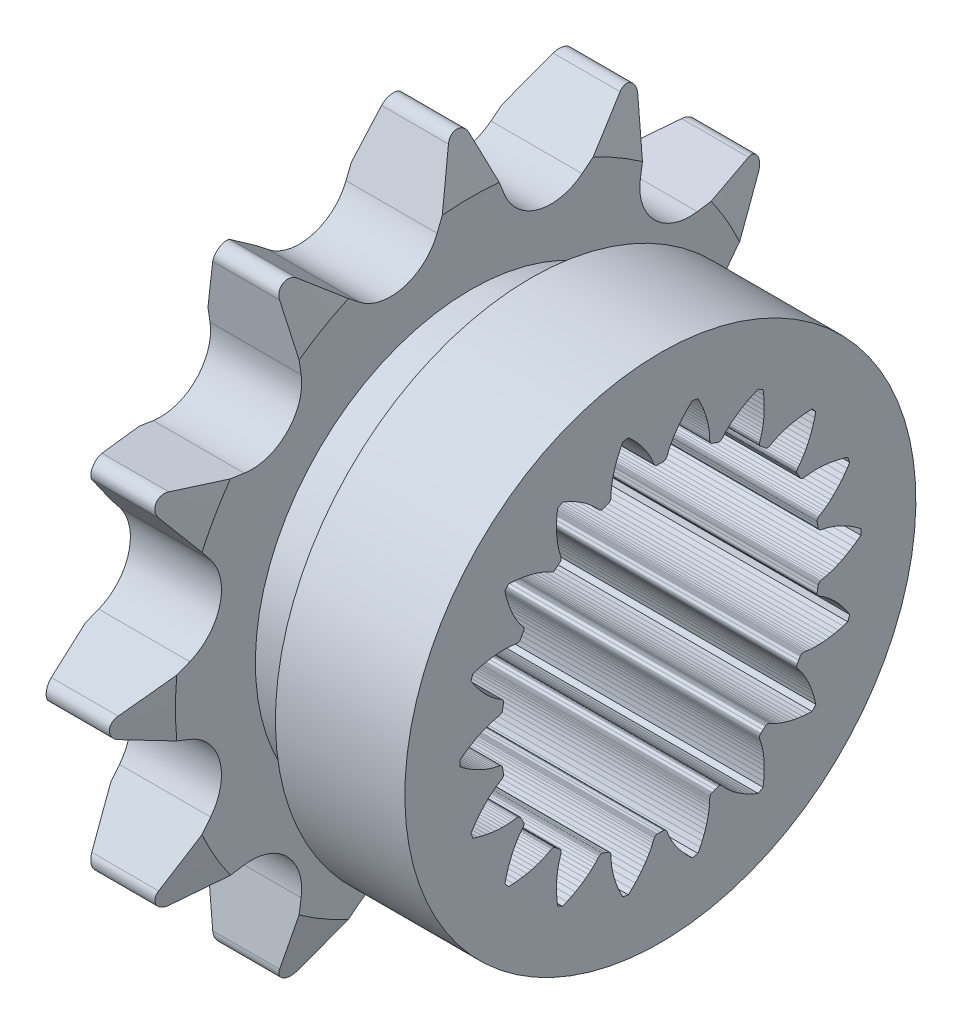
SolidWorks part; units mm, degrees
material "1144"
ref_plane "Front Plane" through (0, 0, 0) normal (0, 0, 1) x (1, 0, 0)
ref_plane "Top Plane" through (0, 0, 0) normal (0, 1, 0) x (1, 0, 0)
ref_plane "Right Plane" through (0, 0, 0) normal (1, 0, 0) x (0, 0, -1)
ref_axis "Axis1" through (-63.0158, 0, 0) along (1, 0, 0)
sketch "Sketch1" plane through (0, 0, 0) normal (0, 0, 1) x (1, 0, 0)
  line L0 (3.6068, 17.0561) -> (3.6068, 0) construction
  line L1 (22.225, 0) -> (22.225, 20.2311)
  line L3 (7.2136, 17.0561) -> (0, 17.0561)
  line L7 (0, 27.5082) -> (0, 30.0482) construction
  line L8 (0, 27.5082) -> (7.2136, 27.5082)
  line L9 (22.225, 0) -> (0, 0)
  line L10 (0, 0) -> (-84.1773, 0) construction
  line L11 (0, 17.0561) -> (0, 27.5082) construction
  line L12 (7.2136, 27.5082) -> (73.2462, 27.5082) construction
  line L13 (22.225, 0) -> (22.225, -20.2311) construction
  line L14 (3.6068, 0) -> (3.6068, -17.0561)
  line L15 (-15.4432, -17.0561) -> (22.6568, -17.0561)
  point P11 (0, 30.0482)
  dimension "D1" = 2.54
  dimension "hub_dia" = 40.4622
  dimension "width_teetth" = 7.2136
  dimension "D2" = 38.1
  dimension "length_thru" = 22.225
  dimension "OD" = 55.0164
  dimension "length_over_teeth" = 7.2136
  dimension "recess_hub_diam" = 34.1122
  dimension "hub_type" = 22.225
  dimension "projection 1" = 15.0114
  dimension "projection 2" = 0
sketch "Sketch2" plane through (0, 0, 0) normal (1, 0, 0) x (0, 0, -1)
  line L0 (0, 0) -> (0, 27.5082) construction
  line L1 (0, 0) -> (-13.7541, 23.8228) construction
  line L2 (0, 0) -> (-6.3502, 23.6991) construction
  line L3 (-0.8057, 26.9597) -> (-2.6638, 22.246)
  line L4 (-2.6638, 22.246) -> (-6.3502, 23.6991) construction
  line L5 (-0.8217, 27.4959) -> (0, 0) construction
  line L6 (-2.735, 27.3719) -> (0, 0) construction
  line L7 (-6.3502, 23.6991) -> (-2.4074, 24.0931) construction
  arc A1 (0, 27.5082) -> (-13.7541, 23.8228) centre (0, 0) ccw
  circle A2 centre (0, 0) radius 24.5351 construction
  circle A3 centre (-6.3502, 23.6991) radius 3.9624
  arc A4 (0, 27.5082) -> (-0.8057, 26.9597) centre (0, 26.6421) ccw
  dimension "pitch_diam" = 49.0703
  dimension "roller_diam" = 7.9248
  dimension "D1" = 1.712
  dimension "ang_1" = 30
  dimension "OD/2" = 27.5082
sketch "Taper Per Foot" plane through (0, 0, 0) normal (0, 0, 1) x (1, 0, 0)
  line L0 (22.225, 0) -> (22.225, 127)
  line L1 (22.225, 0) -> (22.225, 20.2311) construction
  line L2 (22.225, 127) -> (-282.575, 6.35)
  line L3 (-282.575, 6.35) -> (-282.575, 0)
  line L4 (-282.575, 0) -> (22.225, 0)
  line L5 (-282.575, 0) -> (-285.7823, 0) construction
  line L6 (-282.575, 6.35) -> (22.225, 6.35)
  line L7 (22.225, 6.35) -> (22.225, 127)
  dimension "1 Ft" = 304.8
  dimension "1 in" = 254
  dimension "Small End Diam" = 12.7
  dimension "Large End Diam" = 12.7
ref_plane "Plane1" through (7.2136, 0, 0) normal (1, 0, 0) x (0, 0, -1)
ref_plane "Plane2" through (7.2136, 0, 0) normal (1, 0, 0) x (0, 0, -1)
ref_plane "Plane3" through (0, 17.0561, 0) normal (-1, 0, 0) x (0, 0, 1)
ref_plane "Plane4" through (22.225, 0, 0) normal (1, 0, 0) x (0, 0, -1)
ref_plane "Plane5" through (3.6068, 0, 0) normal (1, 0, 0) x (0, 0, -1)
sketch "Sketch13" plane through (0, 0, 0) normal (0, 0, 1) x (1, 0, 0)
  line L0 (22.225, 0) -> (22.225, 20.2311) construction
  line L1 (0, 0) -> (22.225, 0)
  line L2 (0, 0) -> (0, 27.5082)
  line L3 (0, 27.5082) -> (22.225, 27.5082)
  line L4 (22.225, 0) -> (22.225, 27.5082)
revolve "Revolve1" add sketch "Sketch13" angle 360 about L10
sketch "Sketch6" plane through (0, -16.51, 0) normal (1, 0, 0) x (0, 0, -1)
  line L0 (-0.8057, 43.4697) -> (-2.6638, 38.756) construction
  line L1 (-0.8057, 43.4697) -> (-2.6638, 38.756)
  line L2 (-6.3502, 40.2091) -> (0, 16.51) construction
  line L3 (-12.7821, 40.2607) -> (-8.8161, 37.1075)
  arc A0 (0, 44.0182) -> (-0.8057, 43.4697) centre (0, 43.1521) ccw construction
  arc A1 (0, 44.0182) -> (-0.8057, 43.4697) centre (0, 43.1521) ccw
  arc A2 (-13.7541, 40.3328) -> (-12.7821, 40.2607) centre (-13.3211, 39.5828) cw
  arc A3 (-2.6638, 38.756) -> (-8.8161, 37.1075) centre (-6.3502, 40.2091) cw
  arc A4 (0, 44.0182) -> (-13.7541, 40.3328) centre (0, 16.51) ccw
extrude "Cut-Extrude1" cut sketch "Sketch6" along normal up to vertex (7.2136 mm away) up to point (7.2136, 17.0561, 0)
pattern_circular "CirPattern1" count 12 over 360 about axis through (-63.0158, 0, 0) along (1, 0, 0) of "Cut-Extrude1"
sketch "Sketch15" plane through (0, 0, 0) normal (0, 0, 1) x (1, 0, 0)
  line L1 (134.2136, 20.2311) -> (7.2136, 20.2311)
  line L2 (134.2136, 20.2311) -> (134.2136, 42.7482)
  line L3 (134.2136, 42.7482) -> (7.2136, 42.7482)
  line L4 (7.2136, 20.2311) -> (7.2136, 42.7482)
  line L5 (3.6068, 216.4797) -> (3.6068, 17.0561) construction
  line L6 (-127, 20.2311) -> (0, 20.2311)
  line L7 (0, 20.2311) -> (0, 42.7482)
  line L8 (-127, 42.7482) -> (0, 42.7482)
  line L9 (-127, 20.2311) -> (-127, 42.7482)
  dimension "D1" = 12.7
  dimension "D2" = 127
revolve "hub Cut-Revolve3" cut sketch "Sketch15" angle 360 about L10
sketch "Sketch4" plane through (0, 0, 0) normal (0, 0, 1) x (1, 0, 0)
  line L0 (0, 27.5082) -> (1.1045, 27.5082)
  line L2 (1.1045, 27.5082) -> (0, 23.3861)
  line L4 (0, 23.3861) -> (0, 27.5082)
  line L5 (3.6068, 27.5082) -> (3.6068, 44.9612) construction
  line L6 (7.2136, 27.5082) -> (6.1091, 27.5082)
  line L7 (7.2136, 23.3861) -> (7.2136, 27.5082)
  line L8 (6.1091, 27.5082) -> (7.2136, 23.3861)
  line L9 (0, 0) -> (-52.1231, 0) construction
  line L10 (0, 0) -> (-84.1773, 0) construction
  line L17 (0, 27.5082) -> (7.2136, 27.5082) construction
  dimension "D1" = 15
  dimension "D2" = 4.1221
revolve "Teeth Chamfer" cut sketch "Sketch4" angle 360 about L9
sketch "Sketch16" plane through (0, 0, 0) normal (0, 0, 1) x (1, 0, 0)
  line L1 (7.2136, 20.2311) -> (11.9761, 20.2311)
  line L2 (7.2136, 20.2311) -> (7.2136, 17.0561)
  line L3 (7.2136, 17.0561) -> (11.9761, 17.0561)
  line L4 (11.9761, 20.2311) -> (11.9761, 17.0561)
  line L5 (11.9761, 20.2311) -> (22.225, 20.2311) construction
  dimension "recess_width" = 4.7625
  dimension "recess_height" = 3.175
revolve "Recess" cut sketch "Sketch16" angle 360 about L10
sketch "Sketch32" plane through (22.225, 0, 0) normal (1, 0, 0) x (0, 0, -1)
  circle A1 centre (0, 0) radius 20.2311
  circle A2 centre (0, 0) radius 20.2311
  dimension "D1" = 0
extrude "Collar Reduction" [suppressed] cut sketch "Sketch32" against normal offset from surface (2.455 mm away) 19.77 up to face at (0, 0, 0)
ref_plane "Sprocket Teeth Center" through (3.6068, 0, 0) normal (-1, 0, 0) x (0, 0, 1)
sketch "Sketch33" plane through (0, 0, 0) normal (-1, 0, 0) x (0, 0, 1)
  line L0 (14.7873, 4.9) -> (14.564, 4.5862)
  line L1 (14.564, 4.5862) -> (14.3413, 4.2995)
  line L2 (14.3413, 4.2995) -> (14.1194, 4.0373)
  line L3 (14.1194, 4.0373) -> (13.9032, 3.8025)
  line L4 (13.9032, 3.8025) -> (13.6912, 3.5908)
  line L5 (13.6912, 3.5908) -> (13.4871, 3.4033)
  line L6 (13.4871, 3.4033) -> (13.2928, 3.2393)
  line L7 (13.2928, 3.2393) -> (13.1069, 3.0953)
  line L8 (13.1069, 3.0953) -> (12.9349, 2.9732)
  line L9 (12.9349, 2.9732) -> (12.7748, 2.8693)
  line L10 (12.7748, 2.8693) -> (12.6452, 2.7922)
  line L11 (12.6452, 2.7922) -> (12.5432, 2.7214)
  line L12 (12.5432, 2.7214) -> (12.5028, 2.6848)
  line L13 (12.5028, 2.6848) -> (12.4694, 2.6479)
  line L14 (12.4694, 2.6479) -> (12.443, 2.611)
  line L15 (12.443, 2.611) -> (12.4236, 2.5742)
  line L16 (12.4236, 2.5742) -> (12.4112, 2.5378)
  line L17 (12.4112, 2.5378) -> (12.4058, 2.5022)
  line L18 (12.4058, 2.5022) -> (12.4072, 2.4677)
  line L19 (12.4072, 2.4677) -> (12.4155, 2.4245)
  line L20 (12.4155, 2.4245) -> (12.4578, 2.1966)
  line L21 (12.4578, 2.1966) -> (12.496, 1.9681)
  line L22 (12.496, 1.9681) -> (12.503, 1.9247)
  line L23 (12.503, 1.9247) -> (12.5134, 1.8917)
  line L24 (12.5134, 1.8917) -> (12.5307, 1.8601)
  line L25 (12.5307, 1.8601) -> (12.5548, 1.8302)
  line L26 (12.5548, 1.8302) -> (12.5856, 1.8023)
  line L27 (12.5856, 1.8023) -> (12.623, 1.7765)
  line L28 (12.623, 1.7765) -> (12.6671, 1.7533)
  line L29 (12.6671, 1.7533) -> (12.7175, 1.7328)
  line L30 (12.7175, 1.7328) -> (12.8375, 1.7011)
  line L31 (12.8375, 1.7011) -> (12.9858, 1.673)
  line L32 (12.9858, 1.673) -> (13.1717, 1.6301)
  line L33 (13.1717, 1.6301) -> (13.3751, 1.5742)
  line L34 (13.3751, 1.5742) -> (13.5991, 1.5025)
  line L35 (13.5991, 1.5025) -> (13.8378, 1.4148)
  line L36 (13.8378, 1.4148) -> (14.0937, 1.3085)
  line L37 (14.0937, 1.3085) -> (14.3653, 1.182)
  line L38 (14.3653, 1.182) -> (14.6487, 1.0353)
  line L39 (14.6487, 1.0353) -> (14.947, 0.8648)
  line L40 (14.947, 0.8648) -> (15.2543, 0.6715)
  line L41 (15.2543, 0.6715) -> (15.5714, 0.4531)
  line L42 (15.5714, 0.4531) -> (15.8734, 0.2265)
  line L43 (15.8734, -0.2265) -> (15.5714, -0.4531)
  line L44 (15.5714, -0.4531) -> (15.2543, -0.6715)
  line L45 (15.2543, -0.6715) -> (14.947, -0.8648)
  line L46 (14.947, -0.8648) -> (14.6487, -1.0353)
  line L47 (14.6487, -1.0353) -> (14.3653, -1.182)
  line L48 (14.3653, -1.182) -> (14.0937, -1.3085)
  line L49 (14.0937, -1.3085) -> (13.8378, -1.4148)
  line L50 (13.8378, -1.4148) -> (13.5991, -1.5025)
  line L51 (13.5991, -1.5025) -> (13.3751, -1.5742)
  line L52 (13.3751, -1.5742) -> (13.1717, -1.6301)
  line L53 (13.1717, -1.6301) -> (12.9858, -1.673)
  line L54 (12.9858, -1.673) -> (12.8375, -1.7011)
  line L55 (12.8375, -1.7011) -> (12.7175, -1.7328)
  line L56 (12.7175, -1.7328) -> (12.6671, -1.7533)
  line L57 (12.6671, -1.7533) -> (12.623, -1.7765)
  line L58 (12.623, -1.7765) -> (12.5856, -1.8023)
  line L59 (12.5856, -1.8023) -> (12.5548, -1.8302)
  line L60 (12.5548, -1.8302) -> (12.5307, -1.8601)
  line L61 (12.5307, -1.8601) -> (12.5134, -1.8917)
  line L62 (12.5134, -1.8917) -> (12.503, -1.9247)
  line L63 (12.503, -1.9247) -> (12.496, -1.9681)
  line L64 (12.496, -1.9681) -> (12.4578, -2.1966)
  line L65 (12.4578, -2.1966) -> (12.4155, -2.4245)
  line L66 (12.4155, -2.4245) -> (12.4072, -2.4677)
  line L67 (12.4072, -2.4677) -> (12.4058, -2.5022)
  line L68 (12.4058, -2.5022) -> (12.4112, -2.5378)
  line L69 (12.4112, -2.5378) -> (12.4236, -2.5742)
  line L70 (12.4236, -2.5742) -> (12.443, -2.611)
  line L71 (12.443, -2.611) -> (12.4694, -2.6479)
  line L72 (12.4694, -2.6479) -> (12.5028, -2.6848)
  line L73 (12.5028, -2.6848) -> (12.5432, -2.7214)
  line L74 (12.5432, -2.7214) -> (12.6452, -2.7922)
  line L75 (12.6452, -2.7922) -> (12.7748, -2.8693)
  line L76 (12.7748, -2.8693) -> (12.9349, -2.9732)
  line L77 (12.9349, -2.9732) -> (13.1069, -3.0953)
  line L78 (13.1069, -3.0953) -> (13.2928, -3.2393)
  line L79 (13.2928, -3.2393) -> (13.4871, -3.4033)
  line L80 (13.4871, -3.4033) -> (13.6912, -3.5908)
  line L81 (13.6912, -3.5908) -> (13.9032, -3.8025)
  line L82 (13.9032, -3.8025) -> (14.1194, -4.0373)
  line L83 (14.1194, -4.0373) -> (14.3413, -4.2995)
  line L84 (14.3413, -4.2995) -> (14.564, -4.5862)
  line L85 (14.564, -4.5862) -> (14.7873, -4.9)
  line L86 (14.7873, -4.9) -> (14.9936, -5.2162)
  line L87 (14.8386, -5.6419) -> (14.4773, -5.7515)
  line L88 (14.4773, -5.7515) -> (14.1046, -5.8483)
  line L89 (14.1046, -5.8483) -> (13.7498, -5.9248)
  line L90 (13.7498, -5.9248) -> (13.4112, -5.983)
  line L91 (13.4112, -5.983) -> (13.0947, -6.0239)
  line L92 (13.0947, -6.0239) -> (12.7962, -6.0499)
  line L93 (12.7962, -6.0499) -> (12.5194, -6.0623)
  line L94 (12.5194, -6.0623) -> (12.2651, -6.063)
  line L95 (12.2651, -6.063) -> (12.0301, -6.0539)
  line L96 (12.0301, -6.0539) -> (11.8198, -6.0368)
  line L97 (11.8198, -6.0368) -> (11.6305, -6.0135)
  line L98 (11.6305, -6.0135) -> (11.4815, -5.9892)
  line L99 (11.4815, -5.9892) -> (11.3579, -5.978)
  line L100 (11.3579, -5.978) -> (11.3035, -5.9799)
  line L101 (11.3035, -5.9799) -> (11.2542, -5.9867)
  line L102 (11.2542, -5.9867) -> (11.2102, -5.9981)
  line L103 (11.2102, -5.9981) -> (11.1717, -6.0138)
  line L104 (11.1717, -6.0138) -> (11.1388, -6.0337)
  line L105 (11.1388, -6.0337) -> (11.1118, -6.0574)
  line L106 (11.1118, -6.0574) -> (11.0907, -6.0849)
  line L107 (11.0907, -6.0849) -> (11.0693, -6.1233)
  line L108 (11.0693, -6.1233) -> (10.9552, -6.325)
  line L109 (10.9552, -6.325) -> (10.8376, -6.5247)
  line L110 (10.8376, -6.5247) -> (10.815, -6.5624)
  line L111 (10.815, -6.5624) -> (10.8018, -6.5944)
  line L112 (10.8018, -6.5944) -> (10.7947, -6.6297)
  line L113 (10.7947, -6.6297) -> (10.794, -6.668)
  line L114 (10.794, -6.668) -> (10.7996, -6.7092)
  line L115 (10.7996, -6.7092) -> (10.8117, -6.753)
  line L116 (10.8117, -6.753) -> (10.8305, -6.7991)
  line L117 (10.8305, -6.7991) -> (10.856, -6.8473)
  line L118 (10.856, -6.8473) -> (10.9276, -6.9487)
  line L119 (10.9276, -6.9487) -> (11.023, -7.0655)
  line L120 (11.023, -7.0655) -> (11.1379, -7.2178)
  line L121 (11.1379, -7.2178) -> (11.2578, -7.3915)
  line L122 (11.2578, -7.3915) -> (11.3833, -7.5904)
  line L123 (11.3833, -7.5904) -> (11.5098, -7.811)
  line L124 (11.5098, -7.811) -> (11.6374, -8.0569)
  line L125 (11.6374, -8.0569) -> (11.7642, -8.3284)
  line L126 (11.7642, -8.3284) -> (11.8871, -8.6229)
  line L127 (11.8871, -8.6229) -> (12.0059, -8.9453)
  line L128 (12.0059, -8.9453) -> (12.1171, -9.2908)
  line L129 (12.1171, -9.2908) -> (12.2196, -9.662)
  line L130 (12.2196, -9.662) -> (12.3053, -10.0297)
  line L131 (12.0141, -10.3767) -> (11.6371, -10.3562)
  line L132 (11.6371, -10.3562) -> (11.2538, -10.3197)
  line L133 (11.2538, -10.3197) -> (10.8942, -10.2702)
  line L134 (10.8942, -10.2702) -> (10.5561, -10.2091)
  line L135 (10.5561, -10.2091) -> (10.2447, -10.1393)
  line L136 (10.2447, -10.1393) -> (9.9553, -10.0616)
  line L137 (9.9553, -10.0616) -> (9.6909, -9.9785)
  line L138 (9.6909, -9.9785) -> (9.4517, -9.8923)
  line L139 (9.4517, -9.8923) -> (9.2341, -9.8033)
  line L140 (9.2341, -9.8033) -> (9.0423, -9.7154)
  line L141 (9.0423, -9.7154) -> (8.8723, -9.6287)
  line L142 (8.8723, -9.6287) -> (8.7407, -9.5549)
  line L143 (8.7407, -9.5549) -> (8.6284, -9.5021)
  line L144 (8.6284, -9.5021) -> (8.5765, -9.4853)
  line L145 (8.5765, -9.4853) -> (8.5279, -9.4748)
  line L146 (8.5279, -9.4748) -> (8.4826, -9.4705)
  line L147 (8.4826, -9.4705) -> (8.4411, -9.4721)
  line L148 (8.4411, -9.4721) -> (8.4034, -9.4795)
  line L149 (8.4034, -9.4795) -> (8.3699, -9.4926)
  line L150 (8.3699, -9.4926) -> (8.3407, -9.5111)
  line L151 (8.3407, -9.5111) -> (8.3074, -9.5399)
  line L152 (8.3074, -9.5399) -> (8.1313, -9.6905)
  line L153 (8.1313, -9.6905) -> (7.9524, -9.8378)
  line L154 (7.9524, -9.8378) -> (7.9183, -9.8655)
  line L155 (7.9183, -9.8655) -> (7.895, -9.8911)
  line L156 (7.895, -9.8911) -> (7.8763, -9.9219)
  line L157 (7.8763, -9.9219) -> (7.8624, -9.9577)
  line L158 (7.8624, -9.9577) -> (7.8536, -9.9983)
  line L159 (7.8536, -9.9983) -> (7.85, -10.0436)
  line L160 (7.85, -10.0436) -> (7.8519, -10.0933)
  line L161 (7.8519, -10.0933) -> (7.8594, -10.1473)
  line L162 (7.8594, -10.1473) -> (7.892, -10.2671)
  line L163 (7.892, -10.2671) -> (7.9417, -10.4095)
  line L164 (7.9417, -10.4095) -> (7.9976, -10.592)
  line L165 (7.9976, -10.592) -> (8.0509, -10.7961)
  line L166 (8.0509, -10.7961) -> (8.1007, -11.0259)
  line L167 (8.1007, -11.0259) -> (8.1441, -11.2765)
  line L168 (8.1441, -11.2765) -> (8.18, -11.5512)
  line L169 (8.18, -11.5512) -> (8.2063, -11.8497)
  line L170 (8.2063, -11.8497) -> (8.221, -12.1685)
  line L171 (8.221, -12.1685) -> (8.2224, -12.5121)
  line L172 (8.2224, -12.5121) -> (8.2087, -12.8748)
  line L173 (8.2087, -12.8748) -> (8.1781, -13.2587)
  line L174 (8.1781, -13.2587) -> (8.1329, -13.6335)
  line L175 (7.7405, -13.86) -> (7.3933, -13.7118)
  line L176 (7.3933, -13.7118) -> (7.0456, -13.5463)
  line L177 (7.0456, -13.5463) -> (6.7246, -13.3768)
  line L178 (6.7246, -13.3768) -> (6.4278, -13.2038)
  line L179 (6.4278, -13.2038) -> (6.159, -13.0317)
  line L180 (6.159, -13.0317) -> (5.9137, -12.8597)
  line L181 (5.9137, -12.8597) -> (5.6936, -12.6913)
  line L182 (5.6936, -12.6913) -> (5.4984, -12.5284)
  line L183 (5.4984, -12.5284) -> (5.3243, -12.3703)
  line L184 (5.3243, -12.3703) -> (5.1741, -12.2221)
  line L185 (5.1741, -12.2221) -> (5.0441, -12.0825)
  line L186 (5.0441, -12.0825) -> (4.9456, -11.9682)
  line L187 (4.9456, -11.9682) -> (4.8581, -11.8801)
  line L188 (4.8581, -11.8801) -> (4.8151, -11.8466)
  line L189 (4.8151, -11.8466) -> (4.773, -11.8201)
  line L190 (4.773, -11.8201) -> (4.732, -11.8006)
  line L191 (4.732, -11.8006) -> (4.6924, -11.7879)
  line L192 (4.6924, -11.7879) -> (4.6545, -11.782)
  line L193 (4.6545, -11.782) -> (4.6185, -11.7828)
  line L194 (4.6185, -11.7828) -> (4.5847, -11.7902)
  line L195 (4.5847, -11.7902) -> (4.5436, -11.8059)
  line L196 (4.5436, -11.8059) -> (4.3266, -11.8871)
  line L197 (4.3266, -11.8871) -> (4.1081, -11.9644)
  line L198 (4.1081, -11.9644) -> (4.0666, -11.9788)
  line L199 (4.0666, -11.9788) -> (4.0359, -11.9948)
  line L200 (4.0359, -11.9948) -> (4.0078, -12.0173)
  line L201 (4.0078, -12.0173) -> (3.9825, -12.0462)
  line L202 (3.9825, -12.0462) -> (3.9604, -12.0814)
  line L203 (3.9604, -12.0814) -> (3.9415, -12.1228)
  line L204 (3.9415, -12.1228) -> (3.9263, -12.1702)
  line L205 (3.9263, -12.1702) -> (3.9149, -12.2234)
  line L206 (3.9149, -12.2234) -> (3.9045, -12.3471)
  line L207 (3.9045, -12.3471) -> (3.9025, -12.498)
  line L208 (3.9025, -12.498) -> (3.8926, -12.6885)
  line L209 (3.8926, -12.6885) -> (3.8729, -12.8986)
  line L210 (3.8729, -12.8986) -> (3.8411, -13.1316)
  line L211 (3.8411, -13.1316) -> (3.7962, -13.3819)
  line L212 (3.7962, -13.3819) -> (3.7359, -13.6523)
  line L213 (3.7359, -13.6523) -> (3.6585, -13.9418)
  line L214 (3.6585, -13.9418) -> (3.5633, -14.2464)
  line L215 (3.5633, -14.2464) -> (3.4471, -14.5697)
  line L216 (3.4471, -14.5697) -> (3.3102, -14.9059)
  line L217 (3.3102, -14.9059) -> (3.1502, -15.2561)
  line L218 (3.1502, -15.2561) -> (2.9795, -15.5929)
  line L219 (2.5333, -15.6716) -> (2.2577, -15.4135)
  line L220 (2.2577, -15.4135) -> (1.9875, -15.1391)
  line L221 (1.9875, -15.1391) -> (1.7439, -14.8701)
  line L222 (1.7439, -14.8701) -> (1.5241, -14.606)
  line L223 (1.5241, -14.606) -> (1.3305, -14.3523)
  line L224 (1.3305, -14.3523) -> (1.1587, -14.1068)
  line L225 (1.1587, -14.1068) -> (1.0096, -13.8732)
  line L226 (1.0096, -13.8732) -> (0.8818, -13.6534)
  line L227 (0.8818, -13.6534) -> (0.7723, -13.4453)
  line L228 (0.7723, -13.4453) -> (0.6819, -13.2547)
  line L229 (0.6819, -13.2547) -> (0.6074, -13.079)
  line L230 (0.6074, -13.079) -> (0.554, -12.9379)
  line L231 (0.554, -12.9379) -> (0.5019, -12.8252)
  line L232 (0.5019, -12.8252) -> (0.4729, -12.7791)
  line L233 (0.4729, -12.7791) -> (0.4424, -12.7398)
  line L234 (0.4424, -12.7398) -> (0.4106, -12.7074)
  line L235 (0.4106, -12.7074) -> (0.3777, -12.6819)
  line L236 (0.3777, -12.6819) -> (0.3441, -12.6633)
  line L237 (0.3441, -12.6633) -> (0.31, -12.6518)
  line L238 (0.31, -12.6518) -> (0.2757, -12.6472)
  line L239 (0.2757, -12.6472) -> (0.2317, -12.6479)
  line L240 (0.2317, -12.6479) -> (0, -12.65)
  line L241 (0, -12.65) -> (-0.2317, -12.6479)
  line L242 (-0.2317, -12.6479) -> (-0.2757, -12.6472)
  line L243 (-0.2757, -12.6472) -> (-0.31, -12.6518)
  line L244 (-0.31, -12.6518) -> (-0.3441, -12.6633)
  line L245 (-0.3441, -12.6633) -> (-0.3777, -12.6819)
  line L246 (-0.3777, -12.6819) -> (-0.4106, -12.7074)
  line L247 (-0.4106, -12.7074) -> (-0.4424, -12.7398)
  line L248 (-0.4424, -12.7398) -> (-0.4729, -12.7791)
  line L249 (-0.4729, -12.7791) -> (-0.5019, -12.8252)
  line L250 (-0.5019, -12.8252) -> (-0.554, -12.9379)
  line L251 (-0.554, -12.9379) -> (-0.6074, -13.079)
  line L252 (-0.6074, -13.079) -> (-0.6819, -13.2547)
  line L253 (-0.6819, -13.2547) -> (-0.7723, -13.4453)
  line L254 (-0.7723, -13.4453) -> (-0.8818, -13.6534)
  line L255 (-0.8818, -13.6534) -> (-1.0096, -13.8732)
  line L256 (-1.0096, -13.8732) -> (-1.1587, -14.1068)
  line L257 (-1.1587, -14.1068) -> (-1.3305, -14.3523)
  line L258 (-1.3305, -14.3523) -> (-1.5241, -14.606)
  line L259 (-1.5241, -14.606) -> (-1.7439, -14.8701)
  line L260 (-1.7439, -14.8701) -> (-1.9875, -15.1391)
  line L261 (-1.9875, -15.1391) -> (-2.2577, -15.4135)
  line L262 (-2.2577, -15.4135) -> (-2.5333, -15.6716)
  line L263 (-2.9795, -15.5929) -> (-3.1502, -15.2561)
  line L264 (-3.1502, -15.2561) -> (-3.3102, -14.9059)
  line L265 (-3.3102, -14.9059) -> (-3.4471, -14.5697)
  line L266 (-3.4471, -14.5697) -> (-3.5633, -14.2464)
  line L267 (-3.5633, -14.2464) -> (-3.6585, -13.9418)
  line L268 (-3.6585, -13.9418) -> (-3.7359, -13.6523)
  line L269 (-3.7359, -13.6523) -> (-3.7962, -13.3819)
  line L270 (-3.7962, -13.3819) -> (-3.8411, -13.1316)
  line L271 (-3.8411, -13.1316) -> (-3.8729, -12.8986)
  line L272 (-3.8729, -12.8986) -> (-3.8926, -12.6885)
  line L273 (-3.8926, -12.6885) -> (-3.9025, -12.498)
  line L274 (-3.9025, -12.498) -> (-3.9045, -12.3471)
  line L275 (-3.9045, -12.3471) -> (-3.9149, -12.2234)
  line L276 (-3.9149, -12.2234) -> (-3.9263, -12.1702)
  line L277 (-3.9263, -12.1702) -> (-3.9415, -12.1228)
  line L278 (-3.9415, -12.1228) -> (-3.9604, -12.0814)
  line L279 (-3.9604, -12.0814) -> (-3.9825, -12.0462)
  line L280 (-3.9825, -12.0462) -> (-4.0078, -12.0173)
  line L281 (-4.0078, -12.0173) -> (-4.0359, -11.9948)
  line L282 (-4.0359, -11.9948) -> (-4.0666, -11.9788)
  line L283 (-4.0666, -11.9788) -> (-4.1081, -11.9644)
  line L284 (-4.1081, -11.9644) -> (-4.3266, -11.8871)
  line L285 (-4.3266, -11.8871) -> (-4.5436, -11.8059)
  line L286 (-4.5436, -11.8059) -> (-4.5847, -11.7902)
  line L287 (-4.5847, -11.7902) -> (-4.6185, -11.7828)
  line L288 (-4.6185, -11.7828) -> (-4.6545, -11.782)
  line L289 (-4.6545, -11.782) -> (-4.6924, -11.7879)
  line L290 (-4.6924, -11.7879) -> (-4.732, -11.8006)
  line L291 (-4.732, -11.8006) -> (-4.773, -11.8201)
  line L292 (-4.773, -11.8201) -> (-4.8151, -11.8466)
  line L293 (-4.8151, -11.8466) -> (-4.8581, -11.8801)
  line L294 (-4.8581, -11.8801) -> (-4.9456, -11.9682)
  line L295 (-4.9456, -11.9682) -> (-5.0441, -12.0825)
  line L296 (-5.0441, -12.0825) -> (-5.1741, -12.2221)
  line L297 (-5.1741, -12.2221) -> (-5.3243, -12.3703)
  line L298 (-5.3243, -12.3703) -> (-5.4984, -12.5284)
  line L299 (-5.4984, -12.5284) -> (-5.6936, -12.6913)
  line L300 (-5.6936, -12.6913) -> (-5.9137, -12.8597)
  line L301 (-5.9137, -12.8597) -> (-6.159, -13.0317)
  line L302 (-6.159, -13.0317) -> (-6.4278, -13.2038)
  line L303 (-6.4278, -13.2038) -> (-6.7246, -13.3768)
  line L304 (-6.7246, -13.3768) -> (-7.0456, -13.5463)
  line L305 (-7.0456, -13.5463) -> (-7.3933, -13.7118)
  line L306 (-7.3933, -13.7118) -> (-7.7405, -13.86)
  line L307 (-8.1329, -13.6335) -> (-8.1781, -13.2587)
  line L308 (-8.1781, -13.2587) -> (-8.2087, -12.8748)
  line L309 (-8.2087, -12.8748) -> (-8.2224, -12.5121)
  line L310 (-8.2224, -12.5121) -> (-8.221, -12.1685)
  line L311 (-8.221, -12.1685) -> (-8.2063, -11.8497)
  line L312 (-8.2063, -11.8497) -> (-8.18, -11.5512)
  line L313 (-8.18, -11.5512) -> (-8.1441, -11.2765)
  line L314 (-8.1441, -11.2765) -> (-8.1007, -11.0259)
  line L315 (-8.1007, -11.0259) -> (-8.0509, -10.7961)
  line L316 (-8.0509, -10.7961) -> (-7.9976, -10.592)
  line L317 (-7.9976, -10.592) -> (-7.9417, -10.4095)
  line L318 (-7.9417, -10.4095) -> (-7.892, -10.2671)
  line L319 (-7.892, -10.2671) -> (-7.8594, -10.1473)
  line L320 (-7.8594, -10.1473) -> (-7.8519, -10.0933)
  line L321 (-7.8519, -10.0933) -> (-7.85, -10.0436)
  line L322 (-7.85, -10.0436) -> (-7.8536, -9.9983)
  line L323 (-7.8536, -9.9983) -> (-7.8624, -9.9577)
  line L324 (-7.8624, -9.9577) -> (-7.8763, -9.9219)
  line L325 (-7.8763, -9.9219) -> (-7.895, -9.8911)
  line L326 (-7.895, -9.8911) -> (-7.9183, -9.8655)
  line L327 (-7.9183, -9.8655) -> (-7.9524, -9.8378)
  line L328 (-7.9524, -9.8378) -> (-8.1313, -9.6905)
  line L329 (-8.1313, -9.6905) -> (-8.3074, -9.5399)
  line L330 (-8.3074, -9.5399) -> (-8.3407, -9.5111)
  line L331 (-8.3407, -9.5111) -> (-8.3699, -9.4926)
  line L332 (-8.3699, -9.4926) -> (-8.4034, -9.4795)
  line L333 (-8.4034, -9.4795) -> (-8.4411, -9.4721)
  line L334 (-8.4411, -9.4721) -> (-8.4826, -9.4705)
  line L335 (-8.4826, -9.4705) -> (-8.5279, -9.4748)
  line L336 (-8.5279, -9.4748) -> (-8.5765, -9.4853)
  line L337 (-8.5765, -9.4853) -> (-8.6284, -9.5021)
  line L338 (-8.6284, -9.5021) -> (-8.7407, -9.5549)
  line L339 (-8.7407, -9.5549) -> (-8.8723, -9.6287)
  line L340 (-8.8723, -9.6287) -> (-9.0423, -9.7154)
  line L341 (-9.0423, -9.7154) -> (-9.2341, -9.8033)
  line L342 (-9.2341, -9.8033) -> (-9.4517, -9.8923)
  line L343 (-9.4517, -9.8923) -> (-9.6909, -9.9785)
  line L344 (-9.6909, -9.9785) -> (-9.9553, -10.0616)
  line L345 (-9.9553, -10.0616) -> (-10.2447, -10.1393)
  line L346 (-10.2447, -10.1393) -> (-10.5561, -10.2091)
  line L347 (-10.5561, -10.2091) -> (-10.8942, -10.2702)
  line L348 (-10.8942, -10.2702) -> (-11.2538, -10.3197)
  line L349 (-11.2538, -10.3197) -> (-11.6371, -10.3562)
  line L350 (-11.6371, -10.3562) -> (-12.0141, -10.3767)
  line L351 (-12.3053, -10.0297) -> (-12.2196, -9.662)
  line L352 (-12.2196, -9.662) -> (-12.1171, -9.2908)
  line L353 (-12.1171, -9.2908) -> (-12.0059, -8.9453)
  line L354 (-12.0059, -8.9453) -> (-11.8871, -8.6229)
  line L355 (-11.8871, -8.6229) -> (-11.7642, -8.3284)
  line L356 (-11.7642, -8.3284) -> (-11.6374, -8.0569)
  line L357 (-11.6374, -8.0569) -> (-11.5098, -7.811)
  line L358 (-11.5098, -7.811) -> (-11.3833, -7.5904)
  line L359 (-11.3833, -7.5904) -> (-11.2578, -7.3915)
  line L360 (-11.2578, -7.3915) -> (-11.1379, -7.2178)
  line L361 (-11.1379, -7.2178) -> (-11.023, -7.0655)
  line L362 (-11.023, -7.0655) -> (-10.9276, -6.9487)
  line L363 (-10.9276, -6.9487) -> (-10.856, -6.8473)
  line L364 (-10.856, -6.8473) -> (-10.8305, -6.7991)
  line L365 (-10.8305, -6.7991) -> (-10.8117, -6.753)
  line L366 (-10.8117, -6.753) -> (-10.7996, -6.7092)
  line L367 (-10.7996, -6.7092) -> (-10.794, -6.668)
  line L368 (-10.794, -6.668) -> (-10.7947, -6.6297)
  line L369 (-10.7947, -6.6297) -> (-10.8018, -6.5944)
  line L370 (-10.8018, -6.5944) -> (-10.815, -6.5624)
  line L371 (-10.815, -6.5624) -> (-10.8376, -6.5247)
  line L372 (-10.8376, -6.5247) -> (-10.9552, -6.325)
  line L373 (-10.9552, -6.325) -> (-11.0693, -6.1233)
  line L374 (-11.0693, -6.1233) -> (-11.0907, -6.0849)
  line L375 (-11.0907, -6.0849) -> (-11.1118, -6.0574)
  line L376 (-11.1118, -6.0574) -> (-11.1388, -6.0337)
  line L377 (-11.1388, -6.0337) -> (-11.1717, -6.0138)
  line L378 (-11.1717, -6.0138) -> (-11.2102, -5.9981)
  line L379 (-11.2102, -5.9981) -> (-11.2542, -5.9867)
  line L380 (-11.2542, -5.9867) -> (-11.3035, -5.9799)
  line L381 (-11.3035, -5.9799) -> (-11.3579, -5.978)
  line L382 (-11.3579, -5.978) -> (-11.4815, -5.9892)
  line L383 (-11.4815, -5.9892) -> (-11.6305, -6.0135)
  line L384 (-11.6305, -6.0135) -> (-11.8198, -6.0368)
  line L385 (-11.8198, -6.0368) -> (-12.0301, -6.0539)
  line L386 (-12.0301, -6.0539) -> (-12.2651, -6.063)
  line L387 (-12.2651, -6.063) -> (-12.5194, -6.0623)
  line L388 (-12.5194, -6.0623) -> (-12.7962, -6.0499)
  line L389 (-12.7962, -6.0499) -> (-13.0947, -6.0239)
  line L390 (-13.0947, -6.0239) -> (-13.4112, -5.983)
  line L391 (-13.4112, -5.983) -> (-13.7498, -5.9248)
  line L392 (-13.7498, -5.9248) -> (-14.1046, -5.8483)
  line L393 (-14.1046, -5.8483) -> (-14.4773, -5.7515)
  line L394 (-14.4773, -5.7515) -> (-14.8386, -5.6419)
  line L395 (-14.9936, -5.2162) -> (-14.7873, -4.9)
  line L396 (-14.7873, -4.9) -> (-14.564, -4.5862)
  line L397 (-14.564, -4.5862) -> (-14.3413, -4.2995)
  line L398 (-14.3413, -4.2995) -> (-14.1194, -4.0373)
  line L399 (-14.1194, -4.0373) -> (-13.9032, -3.8025)
  line L400 (-13.9032, -3.8025) -> (-13.6912, -3.5908)
  line L401 (-13.6912, -3.5908) -> (-13.4871, -3.4033)
  line L402 (-13.4871, -3.4033) -> (-13.2928, -3.2393)
  line L403 (-13.2928, -3.2393) -> (-13.1069, -3.0953)
  line L404 (-13.1069, -3.0953) -> (-12.9349, -2.9732)
  line L405 (-12.9349, -2.9732) -> (-12.7748, -2.8693)
  line L406 (-12.7748, -2.8693) -> (-12.6452, -2.7922)
  line L407 (-12.6452, -2.7922) -> (-12.5432, -2.7214)
  line L408 (-12.5432, -2.7214) -> (-12.5028, -2.6848)
  line L409 (-12.5028, -2.6848) -> (-12.4694, -2.6479)
  line L410 (-12.4694, -2.6479) -> (-12.443, -2.611)
  line L411 (-12.443, -2.611) -> (-12.4236, -2.5742)
  line L412 (-12.4236, -2.5742) -> (-12.4112, -2.5378)
  line L413 (-12.4112, -2.5378) -> (-12.4058, -2.5022)
  line L414 (-12.4058, -2.5022) -> (-12.4072, -2.4677)
  line L415 (-12.4072, -2.4677) -> (-12.4155, -2.4245)
  line L416 (-12.4155, -2.4245) -> (-12.4578, -2.1966)
  line L417 (-12.4578, -2.1966) -> (-12.496, -1.9681)
  line L418 (-12.496, -1.9681) -> (-12.503, -1.9247)
  line L419 (-12.503, -1.9247) -> (-12.5134, -1.8917)
  line L420 (-12.5134, -1.8917) -> (-12.5307, -1.8601)
  line L421 (-12.5307, -1.8601) -> (-12.5548, -1.8302)
  line L422 (-12.5548, -1.8302) -> (-12.5856, -1.8023)
  line L423 (-12.5856, -1.8023) -> (-12.623, -1.7765)
  line L424 (-12.623, -1.7765) -> (-12.6671, -1.7533)
  line L425 (-12.6671, -1.7533) -> (-12.7175, -1.7328)
  line L426 (-12.7175, -1.7328) -> (-12.8375, -1.7011)
  line L427 (-12.8375, -1.7011) -> (-12.9858, -1.673)
  line L428 (-12.9858, -1.673) -> (-13.1717, -1.6301)
  line L429 (-13.1717, -1.6301) -> (-13.3751, -1.5742)
  line L430 (-13.3751, -1.5742) -> (-13.5991, -1.5025)
  line L431 (-13.5991, -1.5025) -> (-13.8378, -1.4148)
  line L432 (-13.8378, -1.4148) -> (-14.0937, -1.3085)
  line L433 (-14.0937, -1.3085) -> (-14.3653, -1.182)
  line L434 (-14.3653, -1.182) -> (-14.6487, -1.0353)
  line L435 (-14.6487, -1.0353) -> (-14.947, -0.8648)
  line L436 (-14.947, -0.8648) -> (-15.2543, -0.6715)
  line L437 (-15.2543, -0.6715) -> (-15.5714, -0.4531)
  line L438 (-15.5714, -0.4531) -> (-15.8734, -0.2265)
  line L439 (-15.8734, 0.2265) -> (-15.5714, 0.4531)
  line L440 (-15.5714, 0.4531) -> (-15.2543, 0.6715)
  line L441 (-15.2543, 0.6715) -> (-14.947, 0.8648)
  line L442 (-14.947, 0.8648) -> (-14.6487, 1.0353)
  line L443 (-14.6487, 1.0353) -> (-14.3653, 1.182)
  line L444 (-14.3653, 1.182) -> (-14.0937, 1.3085)
  line L445 (-14.0937, 1.3085) -> (-13.8378, 1.4148)
  line L446 (-13.8378, 1.4148) -> (-13.5991, 1.5025)
  line L447 (-13.5991, 1.5025) -> (-13.3751, 1.5742)
  line L448 (-13.3751, 1.5742) -> (-13.1717, 1.6301)
  line L449 (-13.1717, 1.6301) -> (-12.9858, 1.673)
  line L450 (-12.9858, 1.673) -> (-12.8375, 1.7011)
  line L451 (-12.8375, 1.7011) -> (-12.7175, 1.7328)
  line L452 (-12.7175, 1.7328) -> (-12.6671, 1.7533)
  line L453 (-12.6671, 1.7533) -> (-12.623, 1.7765)
  line L454 (-12.623, 1.7765) -> (-12.5856, 1.8023)
  line L455 (-12.5856, 1.8023) -> (-12.5548, 1.8302)
  line L456 (-12.5548, 1.8302) -> (-12.5307, 1.8601)
  line L457 (-12.5307, 1.8601) -> (-12.5134, 1.8917)
  line L458 (-12.5134, 1.8917) -> (-12.503, 1.9247)
  line L459 (-12.503, 1.9247) -> (-12.496, 1.9681)
  line L460 (-12.496, 1.9681) -> (-12.4578, 2.1966)
  line L461 (-12.4578, 2.1966) -> (-12.4155, 2.4245)
  line L462 (-12.4155, 2.4245) -> (-12.4072, 2.4677)
  line L463 (-12.4072, 2.4677) -> (-12.4058, 2.5022)
  line L464 (-12.4058, 2.5022) -> (-12.4112, 2.5378)
  line L465 (-12.4112, 2.5378) -> (-12.4236, 2.5742)
  line L466 (-12.4236, 2.5742) -> (-12.443, 2.611)
  line L467 (-12.443, 2.611) -> (-12.4694, 2.6479)
  line L468 (-12.4694, 2.6479) -> (-12.5028, 2.6848)
  line L469 (-12.5028, 2.6848) -> (-12.5432, 2.7214)
  line L470 (-12.5432, 2.7214) -> (-12.6452, 2.7922)
  line L471 (-12.6452, 2.7922) -> (-12.7748, 2.8693)
  line L472 (-12.7748, 2.8693) -> (-12.9349, 2.9732)
  line L473 (-12.9349, 2.9732) -> (-13.1069, 3.0953)
  line L474 (-13.1069, 3.0953) -> (-13.2928, 3.2393)
  line L475 (-13.2928, 3.2393) -> (-13.4871, 3.4033)
  line L476 (-13.4871, 3.4033) -> (-13.6912, 3.5908)
  line L477 (-13.6912, 3.5908) -> (-13.9032, 3.8025)
  line L478 (-13.9032, 3.8025) -> (-14.1194, 4.0373)
  line L479 (-14.1194, 4.0373) -> (-14.3413, 4.2995)
  line L480 (-14.3413, 4.2995) -> (-14.564, 4.5862)
  line L481 (-14.564, 4.5862) -> (-14.7873, 4.9)
  line L482 (-14.7873, 4.9) -> (-14.9936, 5.2162)
  line L483 (-14.8386, 5.6419) -> (-14.4773, 5.7515)
  line L484 (-14.4773, 5.7515) -> (-14.1046, 5.8483)
  line L485 (-14.1046, 5.8483) -> (-13.7498, 5.9248)
  line L486 (-13.7498, 5.9248) -> (-13.4112, 5.983)
  line L487 (-13.4112, 5.983) -> (-13.0947, 6.0239)
  line L488 (-13.0947, 6.0239) -> (-12.7962, 6.0499)
  line L489 (-12.7962, 6.0499) -> (-12.5194, 6.0623)
  line L490 (-12.5194, 6.0623) -> (-12.2651, 6.063)
  line L491 (-12.2651, 6.063) -> (-12.0301, 6.0539)
  line L492 (-12.0301, 6.0539) -> (-11.8198, 6.0368)
  line L493 (-11.8198, 6.0368) -> (-11.6305, 6.0135)
  line L494 (-11.6305, 6.0135) -> (-11.4815, 5.9892)
  line L495 (-11.4815, 5.9892) -> (-11.3579, 5.978)
  line L496 (-11.3579, 5.978) -> (-11.3035, 5.9799)
  line L497 (-11.3035, 5.9799) -> (-11.2542, 5.9867)
  line L498 (-11.2542, 5.9867) -> (-11.2102, 5.9981)
  line L499 (-11.2102, 5.9981) -> (-11.1717, 6.0138)
  line L500 (-11.1717, 6.0138) -> (-11.1388, 6.0337)
  line L501 (-11.1388, 6.0337) -> (-11.1118, 6.0574)
  line L502 (-11.1118, 6.0574) -> (-11.0907, 6.0849)
  line L503 (-11.0907, 6.0849) -> (-11.0693, 6.1233)
  line L504 (-11.0693, 6.1233) -> (-10.9552, 6.325)
  line L505 (-10.9552, 6.325) -> (-10.8376, 6.5247)
  line L506 (-10.8376, 6.5247) -> (-10.815, 6.5624)
  line L507 (-10.815, 6.5624) -> (-10.8018, 6.5944)
  line L508 (-10.8018, 6.5944) -> (-10.7947, 6.6297)
  line L509 (-10.7947, 6.6297) -> (-10.794, 6.668)
  line L510 (-10.794, 6.668) -> (-10.7996, 6.7092)
  line L511 (-10.7996, 6.7092) -> (-10.8117, 6.753)
  line L512 (-10.8117, 6.753) -> (-10.8305, 6.7991)
  line L513 (-10.8305, 6.7991) -> (-10.856, 6.8473)
  line L514 (-10.856, 6.8473) -> (-10.9276, 6.9487)
  line L515 (-10.9276, 6.9487) -> (-11.023, 7.0655)
  line L516 (-11.023, 7.0655) -> (-11.1379, 7.2178)
  line L517 (-11.1379, 7.2178) -> (-11.2578, 7.3915)
  line L518 (-11.2578, 7.3915) -> (-11.3833, 7.5904)
  line L519 (-11.3833, 7.5904) -> (-11.5098, 7.811)
  line L520 (-11.5098, 7.811) -> (-11.6374, 8.0569)
  line L521 (-11.6374, 8.0569) -> (-11.7642, 8.3284)
  line L522 (-11.7642, 8.3284) -> (-11.8871, 8.6229)
  line L523 (-11.8871, 8.6229) -> (-12.0059, 8.9453)
  line L524 (-12.0059, 8.9453) -> (-12.1171, 9.2908)
  line L525 (-12.1171, 9.2908) -> (-12.2196, 9.662)
  line L526 (-12.2196, 9.662) -> (-12.3053, 10.0297)
  line L527 (-12.0141, 10.3767) -> (-11.6371, 10.3562)
  line L528 (-11.6371, 10.3562) -> (-11.2538, 10.3197)
  line L529 (-11.2538, 10.3197) -> (-10.8942, 10.2702)
  line L530 (-10.8942, 10.2702) -> (-10.5561, 10.2091)
  line L531 (-10.5561, 10.2091) -> (-10.2447, 10.1393)
  line L532 (-10.2447, 10.1393) -> (-9.9553, 10.0616)
  line L533 (-9.9553, 10.0616) -> (-9.6909, 9.9785)
  line L534 (-9.6909, 9.9785) -> (-9.4517, 9.8923)
  line L535 (-9.4517, 9.8923) -> (-9.2341, 9.8033)
  line L536 (-9.2341, 9.8033) -> (-9.0423, 9.7154)
  line L537 (-9.0423, 9.7154) -> (-8.8723, 9.6287)
  line L538 (-8.8723, 9.6287) -> (-8.7407, 9.5549)
  line L539 (-8.7407, 9.5549) -> (-8.6284, 9.5021)
  line L540 (-8.6284, 9.5021) -> (-8.5765, 9.4853)
  line L541 (-8.5765, 9.4853) -> (-8.5279, 9.4748)
  line L542 (-8.5279, 9.4748) -> (-8.4826, 9.4705)
  line L543 (-8.4826, 9.4705) -> (-8.4411, 9.4721)
  line L544 (-8.4411, 9.4721) -> (-8.4034, 9.4795)
  line L545 (-8.4034, 9.4795) -> (-8.3699, 9.4926)
  line L546 (-8.3699, 9.4926) -> (-8.3407, 9.5111)
  line L547 (-8.3407, 9.5111) -> (-8.3074, 9.5399)
  line L548 (-8.3074, 9.5399) -> (-8.1313, 9.6905)
  line L549 (-8.1313, 9.6905) -> (-7.9524, 9.8378)
  line L550 (-7.9524, 9.8378) -> (-7.9183, 9.8655)
  line L551 (-7.9183, 9.8655) -> (-7.895, 9.8911)
  line L552 (-7.895, 9.8911) -> (-7.8763, 9.9219)
  line L553 (-7.8763, 9.9219) -> (-7.8624, 9.9577)
  line L554 (-7.8624, 9.9577) -> (-7.8536, 9.9983)
  line L555 (-7.8536, 9.9983) -> (-7.85, 10.0436)
  line L556 (-7.85, 10.0436) -> (-7.8519, 10.0933)
  line L557 (-7.8519, 10.0933) -> (-7.8594, 10.1473)
  line L558 (-7.8594, 10.1473) -> (-7.892, 10.2671)
  line L559 (-7.892, 10.2671) -> (-7.9417, 10.4095)
  line L560 (-7.9417, 10.4095) -> (-7.9976, 10.592)
  line L561 (-7.9976, 10.592) -> (-8.0509, 10.7961)
  line L562 (-8.0509, 10.7961) -> (-8.1007, 11.0259)
  line L563 (-8.1007, 11.0259) -> (-8.1441, 11.2765)
  line L564 (-8.1441, 11.2765) -> (-8.18, 11.5512)
  line L565 (-8.18, 11.5512) -> (-8.2063, 11.8497)
  line L566 (-8.2063, 11.8497) -> (-8.221, 12.1685)
  line L567 (-8.221, 12.1685) -> (-8.2224, 12.5121)
  line L568 (-8.2224, 12.5121) -> (-8.2087, 12.8748)
  line L569 (-8.2087, 12.8748) -> (-8.1781, 13.2587)
  line L570 (-8.1781, 13.2587) -> (-8.1329, 13.6335)
  line L571 (-7.7405, 13.86) -> (-7.3933, 13.7118)
  line L572 (-7.3933, 13.7118) -> (-7.0456, 13.5463)
  line L573 (-7.0456, 13.5463) -> (-6.7246, 13.3768)
  line L574 (-6.7246, 13.3768) -> (-6.4278, 13.2038)
  line L575 (-6.4278, 13.2038) -> (-6.159, 13.0317)
  line L576 (-6.159, 13.0317) -> (-5.9137, 12.8597)
  line L577 (-5.9137, 12.8597) -> (-5.6936, 12.6913)
  line L578 (-5.6936, 12.6913) -> (-5.4984, 12.5284)
  line L579 (-5.4984, 12.5284) -> (-5.3243, 12.3703)
  line L580 (-5.3243, 12.3703) -> (-5.1741, 12.2221)
  line L581 (-5.1741, 12.2221) -> (-5.0441, 12.0825)
  line L582 (-5.0441, 12.0825) -> (-4.9456, 11.9682)
  line L583 (-4.9456, 11.9682) -> (-4.8581, 11.8801)
  line L584 (-4.8581, 11.8801) -> (-4.8151, 11.8466)
  line L585 (-4.8151, 11.8466) -> (-4.773, 11.8201)
  line L586 (-4.773, 11.8201) -> (-4.732, 11.8006)
  line L587 (-4.732, 11.8006) -> (-4.6924, 11.7879)
  line L588 (-4.6924, 11.7879) -> (-4.6545, 11.782)
  line L589 (-4.6545, 11.782) -> (-4.6185, 11.7828)
  line L590 (-4.6185, 11.7828) -> (-4.5847, 11.7902)
  line L591 (-4.5847, 11.7902) -> (-4.5436, 11.8059)
  line L592 (-4.5436, 11.8059) -> (-4.3266, 11.8871)
  line L593 (-4.3266, 11.8871) -> (-4.1081, 11.9644)
  line L594 (-4.1081, 11.9644) -> (-4.0666, 11.9788)
  line L595 (-4.0666, 11.9788) -> (-4.0359, 11.9948)
  line L596 (-4.0359, 11.9948) -> (-4.0078, 12.0173)
  line L597 (-4.0078, 12.0173) -> (-3.9825, 12.0462)
  line L598 (-3.9825, 12.0462) -> (-3.9604, 12.0814)
  line L599 (-3.9604, 12.0814) -> (-3.9415, 12.1228)
  line L600 (-3.9415, 12.1228) -> (-3.9263, 12.1702)
  line L601 (-3.9263, 12.1702) -> (-3.9149, 12.2234)
  line L602 (-3.9149, 12.2234) -> (-3.9045, 12.3471)
  line L603 (-3.9045, 12.3471) -> (-3.9025, 12.498)
  line L604 (-3.9025, 12.498) -> (-3.8926, 12.6885)
  line L605 (-3.8926, 12.6885) -> (-3.8729, 12.8986)
  line L606 (-3.8729, 12.8986) -> (-3.8411, 13.1316)
  line L607 (-3.8411, 13.1316) -> (-3.7962, 13.3819)
  line L608 (-3.7962, 13.3819) -> (-3.7359, 13.6523)
  line L609 (-3.7359, 13.6523) -> (-3.6585, 13.9418)
  line L610 (-3.6585, 13.9418) -> (-3.5633, 14.2464)
  line L611 (-3.5633, 14.2464) -> (-3.4471, 14.5697)
  line L612 (-3.4471, 14.5697) -> (-3.3102, 14.9059)
  line L613 (-3.3102, 14.9059) -> (-3.1502, 15.2561)
  line L614 (-3.1502, 15.2561) -> (-2.9795, 15.5929)
  line L615 (-2.5333, 15.6716) -> (-2.2577, 15.4135)
  line L616 (-2.2577, 15.4135) -> (-1.9875, 15.1391)
  line L617 (-1.9875, 15.1391) -> (-1.7439, 14.8701)
  line L618 (-1.7439, 14.8701) -> (-1.5241, 14.606)
  line L619 (-1.5241, 14.606) -> (-1.3305, 14.3523)
  line L620 (-1.3305, 14.3523) -> (-1.1587, 14.1068)
  line L621 (-1.1587, 14.1068) -> (-1.0096, 13.8732)
  line L622 (-1.0096, 13.8732) -> (-0.8818, 13.6534)
  line L623 (-0.8818, 13.6534) -> (-0.7723, 13.4453)
  line L624 (-0.7723, 13.4453) -> (-0.6819, 13.2547)
  line L625 (-0.6819, 13.2547) -> (-0.6074, 13.079)
  line L626 (-0.6074, 13.079) -> (-0.554, 12.9379)
  line L627 (-0.554, 12.9379) -> (-0.5019, 12.8252)
  line L628 (-0.5019, 12.8252) -> (-0.4729, 12.7791)
  line L629 (-0.4729, 12.7791) -> (-0.4424, 12.7398)
  line L630 (-0.4424, 12.7398) -> (-0.4106, 12.7074)
  line L631 (-0.4106, 12.7074) -> (-0.3777, 12.6819)
  line L632 (-0.3777, 12.6819) -> (-0.3441, 12.6633)
  line L633 (-0.3441, 12.6633) -> (-0.31, 12.6518)
  line L634 (-0.31, 12.6518) -> (-0.2757, 12.6472)
  line L635 (-0.2757, 12.6472) -> (-0.2317, 12.6479)
  line L636 (-0.2317, 12.6479) -> (0, 12.65)
  line L637 (0, 12.65) -> (0.2317, 12.6479)
  line L638 (0.2317, 12.6479) -> (0.2757, 12.6472)
  line L639 (0.2757, 12.6472) -> (0.31, 12.6518)
  line L640 (0.31, 12.6518) -> (0.3441, 12.6633)
  line L641 (0.3441, 12.6633) -> (0.3777, 12.6819)
  line L642 (0.3777, 12.6819) -> (0.4106, 12.7074)
  line L643 (0.4106, 12.7074) -> (0.4424, 12.7398)
  line L644 (0.4424, 12.7398) -> (0.4729, 12.7791)
  line L645 (0.4729, 12.7791) -> (0.5019, 12.8252)
  line L646 (0.5019, 12.8252) -> (0.554, 12.9379)
  line L647 (0.554, 12.9379) -> (0.6074, 13.079)
  line L648 (0.6074, 13.079) -> (0.6819, 13.2547)
  line L649 (0.6819, 13.2547) -> (0.7723, 13.4453)
  line L650 (0.7723, 13.4453) -> (0.8818, 13.6534)
  line L651 (0.8818, 13.6534) -> (1.0096, 13.8732)
  line L652 (1.0096, 13.8732) -> (1.1587, 14.1068)
  line L653 (1.1587, 14.1068) -> (1.3305, 14.3523)
  line L654 (1.3305, 14.3523) -> (1.5241, 14.606)
  line L655 (1.5241, 14.606) -> (1.7439, 14.8701)
  line L656 (1.7439, 14.8701) -> (1.9875, 15.1391)
  line L657 (1.9875, 15.1391) -> (2.2577, 15.4135)
  line L658 (2.2577, 15.4135) -> (2.5333, 15.6716)
  line L659 (2.9795, 15.5929) -> (3.1502, 15.2561)
  line L660 (3.1502, 15.2561) -> (3.3102, 14.9059)
  line L661 (3.3102, 14.9059) -> (3.4471, 14.5697)
  line L662 (3.4471, 14.5697) -> (3.5633, 14.2464)
  line L663 (3.5633, 14.2464) -> (3.6585, 13.9418)
  line L664 (3.6585, 13.9418) -> (3.7359, 13.6523)
  line L665 (3.7359, 13.6523) -> (3.7962, 13.3819)
  line L666 (3.7962, 13.3819) -> (3.8411, 13.1316)
  line L667 (3.8411, 13.1316) -> (3.8729, 12.8986)
  line L668 (3.8729, 12.8986) -> (3.8926, 12.6885)
  line L669 (3.8926, 12.6885) -> (3.9025, 12.498)
  line L670 (3.9025, 12.498) -> (3.9045, 12.3471)
  line L671 (3.9045, 12.3471) -> (3.9149, 12.2234)
  line L672 (3.9149, 12.2234) -> (3.9263, 12.1702)
  line L673 (3.9263, 12.1702) -> (3.9415, 12.1228)
  line L674 (3.9415, 12.1228) -> (3.9604, 12.0814)
  line L675 (3.9604, 12.0814) -> (3.9825, 12.0462)
  line L676 (3.9825, 12.0462) -> (4.0078, 12.0173)
  line L677 (4.0078, 12.0173) -> (4.0359, 11.9948)
  line L678 (4.0359, 11.9948) -> (4.0666, 11.9788)
  line L679 (4.0666, 11.9788) -> (4.1081, 11.9644)
  line L680 (4.1081, 11.9644) -> (4.3266, 11.8871)
  line L681 (4.3266, 11.8871) -> (4.5436, 11.8059)
  line L682 (4.5436, 11.8059) -> (4.5847, 11.7902)
  line L683 (4.5847, 11.7902) -> (4.6185, 11.7828)
  line L684 (4.6185, 11.7828) -> (4.6545, 11.782)
  line L685 (4.6545, 11.782) -> (4.6924, 11.7879)
  line L686 (4.6924, 11.7879) -> (4.732, 11.8006)
  line L687 (4.732, 11.8006) -> (4.773, 11.8201)
  line L688 (4.773, 11.8201) -> (4.8151, 11.8466)
  line L689 (4.8151, 11.8466) -> (4.8581, 11.8801)
  line L690 (4.8581, 11.8801) -> (4.9456, 11.9682)
  line L691 (4.9456, 11.9682) -> (5.0441, 12.0825)
  line L692 (5.0441, 12.0825) -> (5.1741, 12.2221)
  line L693 (5.1741, 12.2221) -> (5.3243, 12.3703)
  line L694 (5.3243, 12.3703) -> (5.4984, 12.5284)
  line L695 (5.4984, 12.5284) -> (5.6936, 12.6913)
  line L696 (5.6936, 12.6913) -> (5.9137, 12.8597)
  line L697 (5.9137, 12.8597) -> (6.159, 13.0317)
  line L698 (6.159, 13.0317) -> (6.4278, 13.2038)
  line L699 (6.4278, 13.2038) -> (6.7246, 13.3768)
  line L700 (6.7246, 13.3768) -> (7.0456, 13.5463)
  line L701 (7.0456, 13.5463) -> (7.3933, 13.7118)
  line L702 (7.3933, 13.7118) -> (7.7405, 13.86)
  line L703 (8.1329, 13.6335) -> (8.1781, 13.2587)
  line L704 (8.1781, 13.2587) -> (8.2087, 12.8748)
  line L705 (8.2087, 12.8748) -> (8.2224, 12.5121)
  line L706 (8.2224, 12.5121) -> (8.221, 12.1685)
  line L707 (8.221, 12.1685) -> (8.2063, 11.8497)
  line L708 (8.2063, 11.8497) -> (8.18, 11.5512)
  line L709 (8.18, 11.5512) -> (8.1441, 11.2765)
  line L710 (8.1441, 11.2765) -> (8.1007, 11.0259)
  line L711 (8.1007, 11.0259) -> (8.0509, 10.7961)
  line L712 (8.0509, 10.7961) -> (7.9976, 10.592)
  line L713 (7.9976, 10.592) -> (7.9417, 10.4095)
  line L714 (7.9417, 10.4095) -> (7.892, 10.2671)
  line L715 (7.892, 10.2671) -> (7.8594, 10.1473)
  line L716 (7.8594, 10.1473) -> (7.8519, 10.0933)
  line L717 (7.8519, 10.0933) -> (7.85, 10.0436)
  line L718 (7.85, 10.0436) -> (7.8536, 9.9983)
  line L719 (7.8536, 9.9983) -> (7.8624, 9.9577)
  line L720 (7.8624, 9.9577) -> (7.8763, 9.9219)
  line L721 (7.8763, 9.9219) -> (7.895, 9.8911)
  line L722 (7.895, 9.8911) -> (7.9183, 9.8655)
  line L723 (7.9183, 9.8655) -> (7.9524, 9.8378)
  line L724 (7.9524, 9.8378) -> (8.1313, 9.6905)
  line L725 (8.1313, 9.6905) -> (8.3074, 9.5399)
  line L726 (8.3074, 9.5399) -> (8.3407, 9.5111)
  line L727 (8.3407, 9.5111) -> (8.3699, 9.4926)
  line L728 (8.3699, 9.4926) -> (8.4034, 9.4795)
  line L729 (8.4034, 9.4795) -> (8.4411, 9.4721)
  line L730 (8.4411, 9.4721) -> (8.4826, 9.4705)
  line L731 (8.4826, 9.4705) -> (8.5279, 9.4748)
  line L732 (8.5279, 9.4748) -> (8.5765, 9.4853)
  line L733 (8.5765, 9.4853) -> (8.6284, 9.5021)
  line L734 (8.6284, 9.5021) -> (8.7407, 9.5549)
  line L735 (8.7407, 9.5549) -> (8.8723, 9.6287)
  line L736 (8.8723, 9.6287) -> (9.0423, 9.7154)
  line L737 (9.0423, 9.7154) -> (9.2341, 9.8033)
  line L738 (9.2341, 9.8033) -> (9.4517, 9.8923)
  line L739 (9.4517, 9.8923) -> (9.6909, 9.9785)
  line L740 (9.6909, 9.9785) -> (9.9553, 10.0616)
  line L741 (9.9553, 10.0616) -> (10.2447, 10.1393)
  line L742 (10.2447, 10.1393) -> (10.5561, 10.2091)
  line L743 (10.5561, 10.2091) -> (10.8942, 10.2702)
  line L744 (10.8942, 10.2702) -> (11.2538, 10.3197)
  line L745 (11.2538, 10.3197) -> (11.6371, 10.3562)
  line L746 (11.6371, 10.3562) -> (12.0141, 10.3767)
  line L747 (12.3053, 10.0297) -> (12.2196, 9.662)
  line L748 (12.2196, 9.662) -> (12.1171, 9.2908)
  line L749 (12.1171, 9.2908) -> (12.0059, 8.9453)
  line L750 (12.0059, 8.9453) -> (11.8871, 8.6229)
  line L751 (11.8871, 8.6229) -> (11.7642, 8.3284)
  line L752 (11.7642, 8.3284) -> (11.6374, 8.0569)
  line L753 (11.6374, 8.0569) -> (11.5098, 7.811)
  line L754 (11.5098, 7.811) -> (11.3833, 7.5904)
  line L755 (11.3833, 7.5904) -> (11.2578, 7.3915)
  line L756 (11.2578, 7.3915) -> (11.1379, 7.2178)
  line L757 (11.1379, 7.2178) -> (11.023, 7.0655)
  line L758 (11.023, 7.0655) -> (10.9276, 6.9487)
  line L759 (10.9276, 6.9487) -> (10.856, 6.8473)
  line L760 (10.856, 6.8473) -> (10.8305, 6.7991)
  line L761 (10.8305, 6.7991) -> (10.8117, 6.753)
  line L762 (10.8117, 6.753) -> (10.7996, 6.7092)
  line L763 (10.7996, 6.7092) -> (10.794, 6.668)
  line L764 (10.794, 6.668) -> (10.7947, 6.6297)
  line L765 (10.7947, 6.6297) -> (10.8018, 6.5944)
  line L766 (10.8018, 6.5944) -> (10.815, 6.5624)
  line L767 (10.815, 6.5624) -> (10.8376, 6.5247)
  line L768 (10.8376, 6.5247) -> (10.9552, 6.325)
  line L769 (10.9552, 6.325) -> (11.0693, 6.1233)
  line L770 (11.0693, 6.1233) -> (11.0907, 6.0849)
  line L771 (11.0907, 6.0849) -> (11.1118, 6.0574)
  line L772 (11.1118, 6.0574) -> (11.1388, 6.0337)
  line L773 (11.1388, 6.0337) -> (11.1717, 6.0138)
  line L774 (11.1717, 6.0138) -> (11.2102, 5.9981)
  line L775 (11.2102, 5.9981) -> (11.2542, 5.9867)
  line L776 (11.2542, 5.9867) -> (11.3035, 5.9799)
  line L777 (11.3035, 5.9799) -> (11.3579, 5.978)
  line L778 (11.3579, 5.978) -> (11.4815, 5.9892)
  line L779 (11.4815, 5.9892) -> (11.6305, 6.0135)
  line L780 (11.6305, 6.0135) -> (11.8198, 6.0368)
  line L781 (11.8198, 6.0368) -> (12.0301, 6.0539)
  line L782 (12.0301, 6.0539) -> (12.2651, 6.063)
  line L783 (12.2651, 6.063) -> (12.5194, 6.0623)
  line L784 (12.5194, 6.0623) -> (12.7962, 6.0499)
  line L785 (12.7962, 6.0499) -> (13.0947, 6.0239)
  line L786 (13.0947, 6.0239) -> (13.4112, 5.983)
  line L787 (13.4112, 5.983) -> (13.7498, 5.9248)
  line L788 (13.7498, 5.9248) -> (14.1046, 5.8483)
  line L789 (14.1046, 5.8483) -> (14.4773, 5.7515)
  line L790 (14.4773, 5.7515) -> (14.8386, 5.6419)
  line L791 (14.9936, 5.2162) -> (14.7873, 4.9)
  line L792 (14.7873, 4.9) -> (14.564, 4.5862)
  line L793 (14.564, 4.5862) -> (14.3413, 4.2995)
  line L794 (14.3413, 4.2995) -> (14.1194, 4.0373)
  line L795 (14.1194, 4.0373) -> (13.9032, 3.8025)
  line L796 (13.9032, 3.8025) -> (13.6912, 3.5908)
  line L797 (13.6912, 3.5908) -> (13.4871, 3.4033)
  line L798 (13.4871, 3.4033) -> (13.2928, 3.2393)
  line L799 (13.2928, 3.2393) -> (13.1069, 3.0953)
  line L800 (13.1069, 3.0953) -> (12.9349, 2.9732)
  line L801 (12.9349, 2.9732) -> (12.7748, 2.8693)
  line L802 (12.7748, 2.8693) -> (12.6452, 2.7922)
  line L803 (12.6452, 2.7922) -> (12.5432, 2.7214)
  line L804 (12.5432, 2.7214) -> (12.5028, 2.6848)
  line L805 (12.5028, 2.6848) -> (12.4694, 2.6479)
  line L806 (12.4694, 2.6479) -> (12.443, 2.611)
  line L807 (12.443, 2.611) -> (12.4236, 2.5742)
  line L808 (12.4236, 2.5742) -> (12.4112, 2.5378)
  line L809 (12.4112, 2.5378) -> (12.4058, 2.5022)
  line L810 (12.4058, 2.5022) -> (12.4072, 2.4677)
  line L811 (12.4072, 2.4677) -> (12.4155, 2.4245)
  line L812 (12.4155, 2.4245) -> (12.4578, 2.1966)
  line L813 (12.4578, 2.1966) -> (12.496, 1.9681)
  line L814 (12.496, 1.9681) -> (12.503, 1.9247)
  line L815 (12.503, 1.9247) -> (12.5134, 1.8917)
  line L816 (12.5134, 1.8917) -> (12.5307, 1.8601)
  line L817 (12.5307, 1.8601) -> (12.5548, 1.8302)
  line L818 (12.5548, 1.8302) -> (12.5856, 1.8023)
  line L819 (12.5856, 1.8023) -> (12.623, 1.7765)
  line L820 (12.623, 1.7765) -> (12.6671, 1.7533)
  line L821 (12.6671, 1.7533) -> (12.7175, 1.7328)
  line L822 (12.7175, 1.7328) -> (12.8375, 1.7011)
  line L823 (12.8375, 1.7011) -> (12.9858, 1.673)
  line L824 (12.9858, 1.673) -> (13.1717, 1.6301)
  line L825 (13.1717, 1.6301) -> (13.3751, 1.5742)
  line L826 (13.3751, 1.5742) -> (13.5991, 1.5025)
  line L827 (13.5991, 1.5025) -> (13.8378, 1.4148)
  line L828 (13.8378, 1.4148) -> (14.0937, 1.3085)
  line L829 (14.0937, 1.3085) -> (14.3653, 1.182)
  line L830 (14.3653, 1.182) -> (14.6487, 1.0353)
  line L831 (14.6487, 1.0353) -> (14.947, 0.8648)
  line L832 (14.947, 0.8648) -> (15.2543, 0.6715)
  line L833 (15.2543, 0.6715) -> (15.5714, 0.4531)
  line L834 (15.5714, 0.4531) -> (15.8734, 0.2265)
  line L835 (15.8734, -0.2265) -> (15.5714, -0.4531)
  line L836 (15.5714, -0.4531) -> (15.2543, -0.6715)
  line L837 (15.2543, -0.6715) -> (14.947, -0.8648)
  line L838 (14.947, -0.8648) -> (14.6487, -1.0353)
  line L839 (14.6487, -1.0353) -> (14.3653, -1.182)
  line L840 (14.3653, -1.182) -> (14.0937, -1.3085)
  line L841 (14.0937, -1.3085) -> (13.8378, -1.4148)
  line L842 (13.8378, -1.4148) -> (13.5991, -1.5025)
  line L843 (13.5991, -1.5025) -> (13.3751, -1.5742)
  line L844 (13.3751, -1.5742) -> (13.1717, -1.6301)
  line L845 (13.1717, -1.6301) -> (12.9858, -1.673)
  line L846 (12.9858, -1.673) -> (12.8375, -1.7011)
  line L847 (12.8375, -1.7011) -> (12.7175, -1.7328)
  line L848 (12.7175, -1.7328) -> (12.6671, -1.7533)
  line L849 (12.6671, -1.7533) -> (12.623, -1.7765)
  line L850 (12.623, -1.7765) -> (12.5856, -1.8023)
  line L851 (12.5856, -1.8023) -> (12.5548, -1.8302)
  line L852 (12.5548, -1.8302) -> (12.5307, -1.8601)
  line L853 (12.5307, -1.8601) -> (12.5134, -1.8917)
  line L854 (12.5134, -1.8917) -> (12.503, -1.9247)
  line L855 (12.503, -1.9247) -> (12.496, -1.9681)
  line L856 (12.496, -1.9681) -> (12.4578, -2.1966)
  line L857 (12.4578, -2.1966) -> (12.4155, -2.4245)
  line L858 (12.4155, -2.4245) -> (12.4072, -2.4677)
  line L859 (12.4072, -2.4677) -> (12.4058, -2.5022)
  line L860 (12.4058, -2.5022) -> (12.4112, -2.5378)
  line L861 (12.4112, -2.5378) -> (12.4236, -2.5742)
  line L862 (12.4236, -2.5742) -> (12.443, -2.611)
  line L863 (12.443, -2.611) -> (12.4694, -2.6479)
  line L864 (12.4694, -2.6479) -> (12.5028, -2.6848)
  line L865 (12.5028, -2.6848) -> (12.5432, -2.7214)
  line L866 (12.5432, -2.7214) -> (12.6452, -2.7922)
  line L867 (12.6452, -2.7922) -> (12.7748, -2.8693)
  line L868 (12.7748, -2.8693) -> (12.9349, -2.9732)
  line L869 (12.9349, -2.9732) -> (13.1069, -3.0953)
  line L870 (13.1069, -3.0953) -> (13.2928, -3.2393)
  line L871 (13.2928, -3.2393) -> (13.4871, -3.4033)
  line L872 (13.4871, -3.4033) -> (13.6912, -3.5908)
  line L873 (13.6912, -3.5908) -> (13.9032, -3.8025)
  line L874 (13.9032, -3.8025) -> (14.1194, -4.0373)
  line L875 (14.1194, -4.0373) -> (14.3413, -4.2995)
  line L876 (14.3413, -4.2995) -> (14.564, -4.5862)
  line L877 (14.564, -4.5862) -> (14.7873, -4.9)
  line L878 (14.7873, -4.9) -> (14.9936, -5.2162)
  line L879 (14.8386, -5.6419) -> (14.4773, -5.7515)
  line L880 (14.4773, -5.7515) -> (14.1046, -5.8483)
  line L881 (14.1046, -5.8483) -> (13.7498, -5.9248)
  line L882 (13.7498, -5.9248) -> (13.4112, -5.983)
  line L883 (13.4112, -5.983) -> (13.0947, -6.0239)
  line L884 (13.0947, -6.0239) -> (12.7962, -6.0499)
  line L885 (12.7962, -6.0499) -> (12.5194, -6.0623)
  line L886 (12.5194, -6.0623) -> (12.2651, -6.063)
  line L887 (12.2651, -6.063) -> (12.0301, -6.0539)
  line L888 (12.0301, -6.0539) -> (11.8198, -6.0368)
  line L889 (11.8198, -6.0368) -> (11.6305, -6.0135)
  line L890 (11.6305, -6.0135) -> (11.4815, -5.9892)
  line L891 (11.4815, -5.9892) -> (11.3579, -5.978)
  line L892 (11.3579, -5.978) -> (11.3035, -5.9799)
  line L893 (11.3035, -5.9799) -> (11.2542, -5.9867)
  line L894 (11.2542, -5.9867) -> (11.2102, -5.9981)
  line L895 (11.2102, -5.9981) -> (11.1717, -6.0138)
  line L896 (11.1717, -6.0138) -> (11.1388, -6.0337)
  line L897 (11.1388, -6.0337) -> (11.1118, -6.0574)
  line L898 (11.1118, -6.0574) -> (11.0907, -6.0849)
  line L899 (11.0907, -6.0849) -> (11.0693, -6.1233)
  line L900 (11.0693, -6.1233) -> (10.9552, -6.325)
  line L901 (10.9552, -6.325) -> (10.8376, -6.5247)
  line L902 (10.8376, -6.5247) -> (10.815, -6.5624)
  line L903 (10.815, -6.5624) -> (10.8018, -6.5944)
  line L904 (10.8018, -6.5944) -> (10.7947, -6.6297)
  line L905 (10.7947, -6.6297) -> (10.794, -6.668)
  line L906 (10.794, -6.668) -> (10.7996, -6.7092)
  line L907 (10.7996, -6.7092) -> (10.8117, -6.753)
  line L908 (10.8117, -6.753) -> (10.8305, -6.7991)
  line L909 (10.8305, -6.7991) -> (10.856, -6.8473)
  line L910 (10.856, -6.8473) -> (10.9276, -6.9487)
  line L911 (10.9276, -6.9487) -> (11.023, -7.0655)
  line L912 (11.023, -7.0655) -> (11.1379, -7.2178)
  line L913 (11.1379, -7.2178) -> (11.2578, -7.3915)
  line L914 (11.2578, -7.3915) -> (11.3833, -7.5904)
  line L915 (11.3833, -7.5904) -> (11.5098, -7.811)
  line L916 (11.5098, -7.811) -> (11.6374, -8.0569)
  line L917 (11.6374, -8.0569) -> (11.7642, -8.3284)
  line L918 (11.7642, -8.3284) -> (11.8871, -8.6229)
  line L919 (11.8871, -8.6229) -> (12.0059, -8.9453)
  line L920 (12.0059, -8.9453) -> (12.1171, -9.2908)
  line L921 (12.1171, -9.2908) -> (12.2196, -9.662)
  line L922 (12.2196, -9.662) -> (12.3053, -10.0297)
  line L923 (12.0141, -10.3767) -> (11.6371, -10.3562)
  line L924 (11.6371, -10.3562) -> (11.2538, -10.3197)
  line L925 (11.2538, -10.3197) -> (10.8942, -10.2702)
  line L926 (10.8942, -10.2702) -> (10.5561, -10.2091)
  line L927 (10.5561, -10.2091) -> (10.2447, -10.1393)
  line L928 (10.2447, -10.1393) -> (9.9553, -10.0616)
  line L929 (9.9553, -10.0616) -> (9.6909, -9.9785)
  line L930 (9.6909, -9.9785) -> (9.4517, -9.8923)
  line L931 (9.4517, -9.8923) -> (9.2341, -9.8033)
  line L932 (9.2341, -9.8033) -> (9.0423, -9.7154)
  line L933 (9.0423, -9.7154) -> (8.8723, -9.6287)
  line L934 (8.8723, -9.6287) -> (8.7407, -9.5549)
  line L935 (8.7407, -9.5549) -> (8.6284, -9.5021)
  line L936 (8.6284, -9.5021) -> (8.5765, -9.4853)
  line L937 (8.5765, -9.4853) -> (8.5279, -9.4748)
  line L938 (8.5279, -9.4748) -> (8.4826, -9.4705)
  line L939 (8.4826, -9.4705) -> (8.4411, -9.4721)
  line L940 (8.4411, -9.4721) -> (8.4034, -9.4795)
  line L941 (8.4034, -9.4795) -> (8.3699, -9.4926)
  line L942 (8.3699, -9.4926) -> (8.3407, -9.5111)
  line L943 (8.3407, -9.5111) -> (8.3074, -9.5399)
  line L944 (8.3074, -9.5399) -> (8.1313, -9.6905)
  line L945 (8.1313, -9.6905) -> (7.9524, -9.8378)
  line L946 (7.9524, -9.8378) -> (7.9183, -9.8655)
  line L947 (7.9183, -9.8655) -> (7.895, -9.8911)
  line L948 (7.895, -9.8911) -> (7.8763, -9.9219)
  line L949 (7.8763, -9.9219) -> (7.8624, -9.9577)
  line L950 (7.8624, -9.9577) -> (7.8536, -9.9983)
  line L951 (7.8536, -9.9983) -> (7.85, -10.0436)
  line L952 (7.85, -10.0436) -> (7.8519, -10.0933)
  line L953 (7.8519, -10.0933) -> (7.8594, -10.1473)
  line L954 (7.8594, -10.1473) -> (7.892, -10.2671)
  line L955 (7.892, -10.2671) -> (7.9417, -10.4095)
  line L956 (7.9417, -10.4095) -> (7.9976, -10.592)
  line L957 (7.9976, -10.592) -> (8.0509, -10.7961)
  line L958 (8.0509, -10.7961) -> (8.1007, -11.0259)
  line L959 (8.1007, -11.0259) -> (8.1441, -11.2765)
  line L960 (8.1441, -11.2765) -> (8.18, -11.5512)
  line L961 (8.18, -11.5512) -> (8.2063, -11.8497)
  line L962 (8.2063, -11.8497) -> (8.221, -12.1685)
  line L963 (8.221, -12.1685) -> (8.2224, -12.5121)
  line L964 (8.2224, -12.5121) -> (8.2087, -12.8748)
  line L965 (8.2087, -12.8748) -> (8.1781, -13.2587)
  line L966 (8.1781, -13.2587) -> (8.1329, -13.6335)
  line L967 (7.7405, -13.86) -> (7.3933, -13.7118)
  line L968 (7.3933, -13.7118) -> (7.0456, -13.5463)
  line L969 (7.0456, -13.5463) -> (6.7246, -13.3768)
  line L970 (6.7246, -13.3768) -> (6.4278, -13.2038)
  line L971 (6.4278, -13.2038) -> (6.159, -13.0317)
  line L972 (6.159, -13.0317) -> (5.9137, -12.8597)
  line L973 (5.9137, -12.8597) -> (5.6936, -12.6913)
  line L974 (5.6936, -12.6913) -> (5.4984, -12.5284)
  line L975 (5.4984, -12.5284) -> (5.3243, -12.3703)
  line L976 (5.3243, -12.3703) -> (5.1741, -12.2221)
  line L977 (5.1741, -12.2221) -> (5.0441, -12.0825)
  line L978 (5.0441, -12.0825) -> (4.9456, -11.9682)
  line L979 (4.9456, -11.9682) -> (4.8581, -11.8801)
  line L980 (4.8581, -11.8801) -> (4.8151, -11.8466)
  line L981 (4.8151, -11.8466) -> (4.773, -11.8201)
  line L982 (4.773, -11.8201) -> (4.732, -11.8006)
  line L983 (4.732, -11.8006) -> (4.6924, -11.7879)
  line L984 (4.6924, -11.7879) -> (4.6545, -11.782)
  line L985 (4.6545, -11.782) -> (4.6185, -11.7828)
  line L986 (4.6185, -11.7828) -> (4.5847, -11.7902)
  line L987 (4.5847, -11.7902) -> (4.5436, -11.8059)
  line L988 (4.5436, -11.8059) -> (4.3266, -11.8871)
  line L989 (4.3266, -11.8871) -> (4.1081, -11.9644)
  line L990 (4.1081, -11.9644) -> (4.0666, -11.9788)
  line L991 (4.0666, -11.9788) -> (4.0359, -11.9948)
  line L992 (4.0359, -11.9948) -> (4.0078, -12.0173)
  line L993 (4.0078, -12.0173) -> (3.9825, -12.0462)
  line L994 (3.9825, -12.0462) -> (3.9604, -12.0814)
  line L995 (3.9604, -12.0814) -> (3.9415, -12.1228)
  line L996 (3.9415, -12.1228) -> (3.9263, -12.1702)
  line L997 (3.9263, -12.1702) -> (3.9149, -12.2234)
  line L998 (3.9149, -12.2234) -> (3.9045, -12.3471)
  line L999 (3.9045, -12.3471) -> (3.9025, -12.498)
  line L1000 (3.9025, -12.498) -> (3.8926, -12.6885)
  line L1001 (3.8926, -12.6885) -> (3.8729, -12.8986)
  line L1002 (3.8729, -12.8986) -> (3.8411, -13.1316)
  line L1003 (3.8411, -13.1316) -> (3.7962, -13.3819)
  line L1004 (3.7962, -13.3819) -> (3.7359, -13.6523)
  line L1005 (3.7359, -13.6523) -> (3.6585, -13.9418)
  line L1006 (3.6585, -13.9418) -> (3.5633, -14.2464)
  line L1007 (3.5633, -14.2464) -> (3.4471, -14.5697)
  line L1008 (3.4471, -14.5697) -> (3.3102, -14.9059)
  line L1009 (3.3102, -14.9059) -> (3.1502, -15.2561)
  line L1010 (3.1502, -15.2561) -> (2.9795, -15.5929)
  line L1011 (2.5333, -15.6716) -> (2.2577, -15.4135)
  line L1012 (2.2577, -15.4135) -> (1.9875, -15.1391)
  line L1013 (1.9875, -15.1391) -> (1.7439, -14.8701)
  line L1014 (1.7439, -14.8701) -> (1.5241, -14.606)
  line L1015 (1.5241, -14.606) -> (1.3305, -14.3523)
  line L1016 (1.3305, -14.3523) -> (1.1587, -14.1068)
  line L1017 (1.1587, -14.1068) -> (1.0096, -13.8732)
  line L1018 (1.0096, -13.8732) -> (0.8818, -13.6534)
  line L1019 (0.8818, -13.6534) -> (0.7723, -13.4453)
  line L1020 (0.7723, -13.4453) -> (0.6819, -13.2547)
  line L1021 (0.6819, -13.2547) -> (0.6074, -13.079)
  line L1022 (0.6074, -13.079) -> (0.554, -12.9379)
  line L1023 (0.554, -12.9379) -> (0.5019, -12.8252)
  line L1024 (0.5019, -12.8252) -> (0.4729, -12.7791)
  line L1025 (0.4729, -12.7791) -> (0.4424, -12.7398)
  line L1026 (0.4424, -12.7398) -> (0.4106, -12.7074)
  line L1027 (0.4106, -12.7074) -> (0.3777, -12.6819)
  line L1028 (0.3777, -12.6819) -> (0.3441, -12.6633)
  line L1029 (0.3441, -12.6633) -> (0.31, -12.6518)
  line L1030 (0.31, -12.6518) -> (0.2757, -12.6472)
  line L1031 (0.2757, -12.6472) -> (0.2317, -12.6479)
  line L1032 (0.2317, -12.6479) -> (0, -12.65)
  line L1033 (0, -12.65) -> (-0.2317, -12.6479)
  line L1034 (-0.2317, -12.6479) -> (-0.2757, -12.6472)
  line L1035 (-0.2757, -12.6472) -> (-0.31, -12.6518)
  line L1036 (-0.31, -12.6518) -> (-0.3441, -12.6633)
  line L1037 (-0.3441, -12.6633) -> (-0.3777, -12.6819)
  line L1038 (-0.3777, -12.6819) -> (-0.4106, -12.7074)
  line L1039 (-0.4106, -12.7074) -> (-0.4424, -12.7398)
  line L1040 (-0.4424, -12.7398) -> (-0.4729, -12.7791)
  line L1041 (-0.4729, -12.7791) -> (-0.5019, -12.8252)
  line L1042 (-0.5019, -12.8252) -> (-0.554, -12.9379)
  line L1043 (-0.554, -12.9379) -> (-0.6074, -13.079)
  line L1044 (-0.6074, -13.079) -> (-0.6819, -13.2547)
  line L1045 (-0.6819, -13.2547) -> (-0.7723, -13.4453)
  line L1046 (-0.7723, -13.4453) -> (-0.8818, -13.6534)
  line L1047 (-0.8818, -13.6534) -> (-1.0096, -13.8732)
  line L1048 (-1.0096, -13.8732) -> (-1.1587, -14.1068)
  line L1049 (-1.1587, -14.1068) -> (-1.3305, -14.3523)
  line L1050 (-1.3305, -14.3523) -> (-1.5241, -14.606)
  line L1051 (-1.5241, -14.606) -> (-1.7439, -14.8701)
  line L1052 (-1.7439, -14.8701) -> (-1.9875, -15.1391)
  line L1053 (-1.9875, -15.1391) -> (-2.2577, -15.4135)
  line L1054 (-2.2577, -15.4135) -> (-2.5333, -15.6716)
  line L1055 (-2.9795, -15.5929) -> (-3.1502, -15.2561)
  line L1056 (-3.1502, -15.2561) -> (-3.3102, -14.9059)
  line L1057 (-3.3102, -14.9059) -> (-3.4471, -14.5697)
  line L1058 (-3.4471, -14.5697) -> (-3.5633, -14.2464)
  line L1059 (-3.5633, -14.2464) -> (-3.6585, -13.9418)
  line L1060 (-3.6585, -13.9418) -> (-3.7359, -13.6523)
  line L1061 (-3.7359, -13.6523) -> (-3.7962, -13.3819)
  line L1062 (-3.7962, -13.3819) -> (-3.8411, -13.1316)
  line L1063 (-3.8411, -13.1316) -> (-3.8729, -12.8986)
  line L1064 (-3.8729, -12.8986) -> (-3.8926, -12.6885)
  line L1065 (-3.8926, -12.6885) -> (-3.9025, -12.498)
  line L1066 (-3.9025, -12.498) -> (-3.9045, -12.3471)
  line L1067 (-3.9045, -12.3471) -> (-3.9149, -12.2234)
  line L1068 (-3.9149, -12.2234) -> (-3.9263, -12.1702)
  line L1069 (-3.9263, -12.1702) -> (-3.9415, -12.1228)
  line L1070 (-3.9415, -12.1228) -> (-3.9604, -12.0814)
  line L1071 (-3.9604, -12.0814) -> (-3.9825, -12.0462)
  line L1072 (-3.9825, -12.0462) -> (-4.0078, -12.0173)
  line L1073 (-4.0078, -12.0173) -> (-4.0359, -11.9948)
  line L1074 (-4.0359, -11.9948) -> (-4.0666, -11.9788)
  line L1075 (-4.0666, -11.9788) -> (-4.1081, -11.9644)
  line L1076 (-4.1081, -11.9644) -> (-4.3266, -11.8871)
  line L1077 (-4.3266, -11.8871) -> (-4.5436, -11.8059)
  line L1078 (-4.5436, -11.8059) -> (-4.5847, -11.7902)
  line L1079 (-4.5847, -11.7902) -> (-4.6185, -11.7828)
  line L1080 (-4.6185, -11.7828) -> (-4.6545, -11.782)
  line L1081 (-4.6545, -11.782) -> (-4.6924, -11.7879)
  line L1082 (-4.6924, -11.7879) -> (-4.732, -11.8006)
  line L1083 (-4.732, -11.8006) -> (-4.773, -11.8201)
  line L1084 (-4.773, -11.8201) -> (-4.8151, -11.8466)
  line L1085 (-4.8151, -11.8466) -> (-4.8581, -11.8801)
  line L1086 (-4.8581, -11.8801) -> (-4.9456, -11.9682)
  line L1087 (-4.9456, -11.9682) -> (-5.0441, -12.0825)
  line L1088 (-5.0441, -12.0825) -> (-5.1741, -12.2221)
  line L1089 (-5.1741, -12.2221) -> (-5.3243, -12.3703)
  line L1090 (-5.3243, -12.3703) -> (-5.4984, -12.5284)
  line L1091 (-5.4984, -12.5284) -> (-5.6936, -12.6913)
  line L1092 (-5.6936, -12.6913) -> (-5.9137, -12.8597)
  line L1093 (-5.9137, -12.8597) -> (-6.159, -13.0317)
  line L1094 (-6.159, -13.0317) -> (-6.4278, -13.2038)
  line L1095 (-6.4278, -13.2038) -> (-6.7246, -13.3768)
  line L1096 (-6.7246, -13.3768) -> (-7.0456, -13.5463)
  line L1097 (-7.0456, -13.5463) -> (-7.3933, -13.7118)
  line L1098 (-7.3933, -13.7118) -> (-7.7405, -13.86)
  line L1099 (-8.1329, -13.6335) -> (-8.1781, -13.2587)
  line L1100 (-8.1781, -13.2587) -> (-8.2087, -12.8748)
  line L1101 (-8.2087, -12.8748) -> (-8.2224, -12.5121)
  line L1102 (-8.2224, -12.5121) -> (-8.221, -12.1685)
  line L1103 (-8.221, -12.1685) -> (-8.2063, -11.8497)
  line L1104 (-8.2063, -11.8497) -> (-8.18, -11.5512)
  line L1105 (-8.18, -11.5512) -> (-8.1441, -11.2765)
  line L1106 (-8.1441, -11.2765) -> (-8.1007, -11.0259)
  line L1107 (-8.1007, -11.0259) -> (-8.0509, -10.7961)
  line L1108 (-8.0509, -10.7961) -> (-7.9976, -10.592)
  line L1109 (-7.9976, -10.592) -> (-7.9417, -10.4095)
  line L1110 (-7.9417, -10.4095) -> (-7.892, -10.2671)
  line L1111 (-7.892, -10.2671) -> (-7.8594, -10.1473)
  line L1112 (-7.8594, -10.1473) -> (-7.8519, -10.0933)
  line L1113 (-7.8519, -10.0933) -> (-7.85, -10.0436)
  line L1114 (-7.85, -10.0436) -> (-7.8536, -9.9983)
  line L1115 (-7.8536, -9.9983) -> (-7.8624, -9.9577)
  line L1116 (-7.8624, -9.9577) -> (-7.8763, -9.9219)
  line L1117 (-7.8763, -9.9219) -> (-7.895, -9.8911)
  line L1118 (-7.895, -9.8911) -> (-7.9183, -9.8655)
  line L1119 (-7.9183, -9.8655) -> (-7.9524, -9.8378)
  line L1120 (-7.9524, -9.8378) -> (-8.1313, -9.6905)
  line L1121 (-8.1313, -9.6905) -> (-8.3074, -9.5399)
  line L1122 (-8.3074, -9.5399) -> (-8.3407, -9.5111)
  line L1123 (-8.3407, -9.5111) -> (-8.3699, -9.4926)
  line L1124 (-8.3699, -9.4926) -> (-8.4034, -9.4795)
  line L1125 (-8.4034, -9.4795) -> (-8.4411, -9.4721)
  line L1126 (-8.4411, -9.4721) -> (-8.4826, -9.4705)
  line L1127 (-8.4826, -9.4705) -> (-8.5279, -9.4748)
  line L1128 (-8.5279, -9.4748) -> (-8.5765, -9.4853)
  line L1129 (-8.5765, -9.4853) -> (-8.6284, -9.5021)
  line L1130 (-8.6284, -9.5021) -> (-8.7407, -9.5549)
  line L1131 (-8.7407, -9.5549) -> (-8.8723, -9.6287)
  line L1132 (-8.8723, -9.6287) -> (-9.0423, -9.7154)
  line L1133 (-9.0423, -9.7154) -> (-9.2341, -9.8033)
  line L1134 (-9.2341, -9.8033) -> (-9.4517, -9.8923)
  line L1135 (-9.4517, -9.8923) -> (-9.6909, -9.9785)
  line L1136 (-9.6909, -9.9785) -> (-9.9553, -10.0616)
  line L1137 (-9.9553, -10.0616) -> (-10.2447, -10.1393)
  line L1138 (-10.2447, -10.1393) -> (-10.5561, -10.2091)
  line L1139 (-10.5561, -10.2091) -> (-10.8942, -10.2702)
  line L1140 (-10.8942, -10.2702) -> (-11.2538, -10.3197)
  line L1141 (-11.2538, -10.3197) -> (-11.6371, -10.3562)
  line L1142 (-11.6371, -10.3562) -> (-12.0141, -10.3767)
  line L1143 (-12.3053, -10.0297) -> (-12.2196, -9.662)
  line L1144 (-12.2196, -9.662) -> (-12.1171, -9.2908)
  line L1145 (-12.1171, -9.2908) -> (-12.0059, -8.9453)
  line L1146 (-12.0059, -8.9453) -> (-11.8871, -8.6229)
  line L1147 (-11.8871, -8.6229) -> (-11.7642, -8.3284)
  line L1148 (-11.7642, -8.3284) -> (-11.6374, -8.0569)
  line L1149 (-11.6374, -8.0569) -> (-11.5098, -7.811)
  line L1150 (-11.5098, -7.811) -> (-11.3833, -7.5904)
  line L1151 (-11.3833, -7.5904) -> (-11.2578, -7.3915)
  line L1152 (-11.2578, -7.3915) -> (-11.1379, -7.2178)
  line L1153 (-11.1379, -7.2178) -> (-11.023, -7.0655)
  line L1154 (-11.023, -7.0655) -> (-10.9276, -6.9487)
  line L1155 (-10.9276, -6.9487) -> (-10.856, -6.8473)
  line L1156 (-10.856, -6.8473) -> (-10.8305, -6.7991)
  line L1157 (-10.8305, -6.7991) -> (-10.8117, -6.753)
  line L1158 (-10.8117, -6.753) -> (-10.7996, -6.7092)
  line L1159 (-10.7996, -6.7092) -> (-10.794, -6.668)
  line L1160 (-10.794, -6.668) -> (-10.7947, -6.6297)
  line L1161 (-10.7947, -6.6297) -> (-10.8018, -6.5944)
  line L1162 (-10.8018, -6.5944) -> (-10.815, -6.5624)
  line L1163 (-10.815, -6.5624) -> (-10.8376, -6.5247)
  line L1164 (-10.8376, -6.5247) -> (-10.9552, -6.325)
  line L1165 (-10.9552, -6.325) -> (-11.0693, -6.1233)
  line L1166 (-11.0693, -6.1233) -> (-11.0907, -6.0849)
  line L1167 (-11.0907, -6.0849) -> (-11.1118, -6.0574)
  line L1168 (-11.1118, -6.0574) -> (-11.1388, -6.0337)
  line L1169 (-11.1388, -6.0337) -> (-11.1717, -6.0138)
  line L1170 (-11.1717, -6.0138) -> (-11.2102, -5.9981)
  line L1171 (-11.2102, -5.9981) -> (-11.2542, -5.9867)
  line L1172 (-11.2542, -5.9867) -> (-11.3035, -5.9799)
  line L1173 (-11.3035, -5.9799) -> (-11.3579, -5.978)
  line L1174 (-11.3579, -5.978) -> (-11.4815, -5.9892)
  line L1175 (-11.4815, -5.9892) -> (-11.6305, -6.0135)
  line L1176 (-11.6305, -6.0135) -> (-11.8198, -6.0368)
  line L1177 (-11.8198, -6.0368) -> (-12.0301, -6.0539)
  line L1178 (-12.0301, -6.0539) -> (-12.2651, -6.063)
  line L1179 (-12.2651, -6.063) -> (-12.5194, -6.0623)
  line L1180 (-12.5194, -6.0623) -> (-12.7962, -6.0499)
  line L1181 (-12.7962, -6.0499) -> (-13.0947, -6.0239)
  line L1182 (-13.0947, -6.0239) -> (-13.4112, -5.983)
  line L1183 (-13.4112, -5.983) -> (-13.7498, -5.9248)
  line L1184 (-13.7498, -5.9248) -> (-14.1046, -5.8483)
  line L1185 (-14.1046, -5.8483) -> (-14.4773, -5.7515)
  line L1186 (-14.4773, -5.7515) -> (-14.8386, -5.6419)
  line L1187 (-14.9936, -5.2162) -> (-14.7873, -4.9)
  line L1188 (-14.7873, -4.9) -> (-14.564, -4.5862)
  line L1189 (-14.564, -4.5862) -> (-14.3413, -4.2995)
  line L1190 (-14.3413, -4.2995) -> (-14.1194, -4.0373)
  line L1191 (-14.1194, -4.0373) -> (-13.9032, -3.8025)
  line L1192 (-13.9032, -3.8025) -> (-13.6912, -3.5908)
  line L1193 (-13.6912, -3.5908) -> (-13.4871, -3.4033)
  line L1194 (-13.4871, -3.4033) -> (-13.2928, -3.2393)
  line L1195 (-13.2928, -3.2393) -> (-13.1069, -3.0953)
  line L1196 (-13.1069, -3.0953) -> (-12.9349, -2.9732)
  line L1197 (-12.9349, -2.9732) -> (-12.7748, -2.8693)
  line L1198 (-12.7748, -2.8693) -> (-12.6452, -2.7922)
  line L1199 (-12.6452, -2.7922) -> (-12.5432, -2.7214)
  line L1200 (-12.5432, -2.7214) -> (-12.5028, -2.6848)
  line L1201 (-12.5028, -2.6848) -> (-12.4694, -2.6479)
  line L1202 (-12.4694, -2.6479) -> (-12.443, -2.611)
  line L1203 (-12.443, -2.611) -> (-12.4236, -2.5742)
  line L1204 (-12.4236, -2.5742) -> (-12.4112, -2.5378)
  line L1205 (-12.4112, -2.5378) -> (-12.4058, -2.5022)
  line L1206 (-12.4058, -2.5022) -> (-12.4072, -2.4677)
  line L1207 (-12.4072, -2.4677) -> (-12.4155, -2.4245)
  line L1208 (-12.4155, -2.4245) -> (-12.4578, -2.1966)
  line L1209 (-12.4578, -2.1966) -> (-12.496, -1.9681)
  line L1210 (-12.496, -1.9681) -> (-12.503, -1.9247)
  line L1211 (-12.503, -1.9247) -> (-12.5134, -1.8917)
  line L1212 (-12.5134, -1.8917) -> (-12.5307, -1.8601)
  line L1213 (-12.5307, -1.8601) -> (-12.5548, -1.8302)
  line L1214 (-12.5548, -1.8302) -> (-12.5856, -1.8023)
  line L1215 (-12.5856, -1.8023) -> (-12.623, -1.7765)
  line L1216 (-12.623, -1.7765) -> (-12.6671, -1.7533)
  line L1217 (-12.6671, -1.7533) -> (-12.7175, -1.7328)
  line L1218 (-12.7175, -1.7328) -> (-12.8375, -1.7011)
  line L1219 (-12.8375, -1.7011) -> (-12.9858, -1.673)
  line L1220 (-12.9858, -1.673) -> (-13.1717, -1.6301)
  line L1221 (-13.1717, -1.6301) -> (-13.3751, -1.5742)
  line L1222 (-13.3751, -1.5742) -> (-13.5991, -1.5025)
  line L1223 (-13.5991, -1.5025) -> (-13.8378, -1.4148)
  line L1224 (-13.8378, -1.4148) -> (-14.0937, -1.3085)
  line L1225 (-14.0937, -1.3085) -> (-14.3653, -1.182)
  line L1226 (-14.3653, -1.182) -> (-14.6487, -1.0353)
  line L1227 (-14.6487, -1.0353) -> (-14.947, -0.8648)
  line L1228 (-14.947, -0.8648) -> (-15.2543, -0.6715)
  line L1229 (-15.2543, -0.6715) -> (-15.5714, -0.4531)
  line L1230 (-15.5714, -0.4531) -> (-15.8734, -0.2265)
  line L1231 (-15.8734, 0.2265) -> (-15.5714, 0.4531)
  line L1232 (-15.5714, 0.4531) -> (-15.2543, 0.6715)
  line L1233 (-15.2543, 0.6715) -> (-14.947, 0.8648)
  line L1234 (-14.947, 0.8648) -> (-14.6487, 1.0353)
  line L1235 (-14.6487, 1.0353) -> (-14.3653, 1.182)
  line L1236 (-14.3653, 1.182) -> (-14.0937, 1.3085)
  line L1237 (-14.0937, 1.3085) -> (-13.8378, 1.4148)
  line L1238 (-13.8378, 1.4148) -> (-13.5991, 1.5025)
  line L1239 (-13.5991, 1.5025) -> (-13.3751, 1.5742)
  line L1240 (-13.3751, 1.5742) -> (-13.1717, 1.6301)
  line L1241 (-13.1717, 1.6301) -> (-12.9858, 1.673)
  line L1242 (-12.9858, 1.673) -> (-12.8375, 1.7011)
  line L1243 (-12.8375, 1.7011) -> (-12.7175, 1.7328)
  line L1244 (-12.7175, 1.7328) -> (-12.6671, 1.7533)
  line L1245 (-12.6671, 1.7533) -> (-12.623, 1.7765)
  line L1246 (-12.623, 1.7765) -> (-12.5856, 1.8023)
  line L1247 (-12.5856, 1.8023) -> (-12.5548, 1.8302)
  line L1248 (-12.5548, 1.8302) -> (-12.5307, 1.8601)
  line L1249 (-12.5307, 1.8601) -> (-12.5134, 1.8917)
  line L1250 (-12.5134, 1.8917) -> (-12.503, 1.9247)
  line L1251 (-12.503, 1.9247) -> (-12.496, 1.9681)
  line L1252 (-12.496, 1.9681) -> (-12.4578, 2.1966)
  line L1253 (-12.4578, 2.1966) -> (-12.4155, 2.4245)
  line L1254 (-12.4155, 2.4245) -> (-12.4072, 2.4677)
  line L1255 (-12.4072, 2.4677) -> (-12.4058, 2.5022)
  line L1256 (-12.4058, 2.5022) -> (-12.4112, 2.5378)
  line L1257 (-12.4112, 2.5378) -> (-12.4236, 2.5742)
  line L1258 (-12.4236, 2.5742) -> (-12.443, 2.611)
  line L1259 (-12.443, 2.611) -> (-12.4694, 2.6479)
  line L1260 (-12.4694, 2.6479) -> (-12.5028, 2.6848)
  line L1261 (-12.5028, 2.6848) -> (-12.5432, 2.7214)
  line L1262 (-12.5432, 2.7214) -> (-12.6452, 2.7922)
  line L1263 (-12.6452, 2.7922) -> (-12.7748, 2.8693)
  line L1264 (-12.7748, 2.8693) -> (-12.9349, 2.9732)
  line L1265 (-12.9349, 2.9732) -> (-13.1069, 3.0953)
  line L1266 (-13.1069, 3.0953) -> (-13.2928, 3.2393)
  line L1267 (-13.2928, 3.2393) -> (-13.4871, 3.4033)
  line L1268 (-13.4871, 3.4033) -> (-13.6912, 3.5908)
  line L1269 (-13.6912, 3.5908) -> (-13.9032, 3.8025)
  line L1270 (-13.9032, 3.8025) -> (-14.1194, 4.0373)
  line L1271 (-14.1194, 4.0373) -> (-14.3413, 4.2995)
  line L1272 (-14.3413, 4.2995) -> (-14.564, 4.5862)
  line L1273 (-14.564, 4.5862) -> (-14.7873, 4.9)
  line L1274 (-14.7873, 4.9) -> (-14.9936, 5.2162)
  line L1275 (-14.8386, 5.6419) -> (-14.4773, 5.7515)
  line L1276 (-14.4773, 5.7515) -> (-14.1046, 5.8483)
  line L1277 (-14.1046, 5.8483) -> (-13.7498, 5.9248)
  line L1278 (-13.7498, 5.9248) -> (-13.4112, 5.983)
  line L1279 (-13.4112, 5.983) -> (-13.0947, 6.0239)
  line L1280 (-13.0947, 6.0239) -> (-12.7962, 6.0499)
  line L1281 (-12.7962, 6.0499) -> (-12.5194, 6.0623)
  line L1282 (-12.5194, 6.0623) -> (-12.2651, 6.063)
  line L1283 (-12.2651, 6.063) -> (-12.0301, 6.0539)
  line L1284 (-12.0301, 6.0539) -> (-11.8198, 6.0368)
  line L1285 (-11.8198, 6.0368) -> (-11.6305, 6.0135)
  line L1286 (-11.6305, 6.0135) -> (-11.4815, 5.9892)
  line L1287 (-11.4815, 5.9892) -> (-11.3579, 5.978)
  line L1288 (-11.3579, 5.978) -> (-11.3035, 5.9799)
  line L1289 (-11.3035, 5.9799) -> (-11.2542, 5.9867)
  line L1290 (-11.2542, 5.9867) -> (-11.2102, 5.9981)
  line L1291 (-11.2102, 5.9981) -> (-11.1717, 6.0138)
  line L1292 (-11.1717, 6.0138) -> (-11.1388, 6.0337)
  line L1293 (-11.1388, 6.0337) -> (-11.1118, 6.0574)
  line L1294 (-11.1118, 6.0574) -> (-11.0907, 6.0849)
  line L1295 (-11.0907, 6.0849) -> (-11.0693, 6.1233)
  line L1296 (-11.0693, 6.1233) -> (-10.9552, 6.325)
  line L1297 (-10.9552, 6.325) -> (-10.8376, 6.5247)
  line L1298 (-10.8376, 6.5247) -> (-10.815, 6.5624)
  line L1299 (-10.815, 6.5624) -> (-10.8018, 6.5944)
  line L1300 (-10.8018, 6.5944) -> (-10.7947, 6.6297)
  line L1301 (-10.7947, 6.6297) -> (-10.794, 6.668)
  line L1302 (-10.794, 6.668) -> (-10.7996, 6.7092)
  line L1303 (-10.7996, 6.7092) -> (-10.8117, 6.753)
  line L1304 (-10.8117, 6.753) -> (-10.8305, 6.7991)
  line L1305 (-10.8305, 6.7991) -> (-10.856, 6.8473)
  line L1306 (-10.856, 6.8473) -> (-10.9276, 6.9487)
  line L1307 (-10.9276, 6.9487) -> (-11.023, 7.0655)
  line L1308 (-11.023, 7.0655) -> (-11.1379, 7.2178)
  line L1309 (-11.1379, 7.2178) -> (-11.2578, 7.3915)
  line L1310 (-11.2578, 7.3915) -> (-11.3833, 7.5904)
  line L1311 (-11.3833, 7.5904) -> (-11.5098, 7.811)
  line L1312 (-11.5098, 7.811) -> (-11.6374, 8.0569)
  line L1313 (-11.6374, 8.0569) -> (-11.7642, 8.3284)
  line L1314 (-11.7642, 8.3284) -> (-11.8871, 8.6229)
  line L1315 (-11.8871, 8.6229) -> (-12.0059, 8.9453)
  line L1316 (-12.0059, 8.9453) -> (-12.1171, 9.2908)
  line L1317 (-12.1171, 9.2908) -> (-12.2196, 9.662)
  line L1318 (-12.2196, 9.662) -> (-12.3053, 10.0297)
  line L1319 (-12.0141, 10.3767) -> (-11.6371, 10.3562)
  line L1320 (-11.6371, 10.3562) -> (-11.2538, 10.3197)
  line L1321 (-11.2538, 10.3197) -> (-10.8942, 10.2702)
  line L1322 (-10.8942, 10.2702) -> (-10.5561, 10.2091)
  line L1323 (-10.5561, 10.2091) -> (-10.2447, 10.1393)
  line L1324 (-10.2447, 10.1393) -> (-9.9553, 10.0616)
  line L1325 (-9.9553, 10.0616) -> (-9.6909, 9.9785)
  line L1326 (-9.6909, 9.9785) -> (-9.4517, 9.8923)
  line L1327 (-9.4517, 9.8923) -> (-9.2341, 9.8033)
  line L1328 (-9.2341, 9.8033) -> (-9.0423, 9.7154)
  line L1329 (-9.0423, 9.7154) -> (-8.8723, 9.6287)
  line L1330 (-8.8723, 9.6287) -> (-8.7407, 9.5549)
  line L1331 (-8.7407, 9.5549) -> (-8.6284, 9.5021)
  line L1332 (-8.6284, 9.5021) -> (-8.5765, 9.4853)
  line L1333 (-8.5765, 9.4853) -> (-8.5279, 9.4748)
  line L1334 (-8.5279, 9.4748) -> (-8.4826, 9.4705)
  line L1335 (-8.4826, 9.4705) -> (-8.4411, 9.4721)
  line L1336 (-8.4411, 9.4721) -> (-8.4034, 9.4795)
  line L1337 (-8.4034, 9.4795) -> (-8.3699, 9.4926)
  line L1338 (-8.3699, 9.4926) -> (-8.3407, 9.5111)
  line L1339 (-8.3407, 9.5111) -> (-8.3074, 9.5399)
  line L1340 (-8.3074, 9.5399) -> (-8.1313, 9.6905)
  line L1341 (-8.1313, 9.6905) -> (-7.9524, 9.8378)
  line L1342 (-7.9524, 9.8378) -> (-7.9183, 9.8655)
  line L1343 (-7.9183, 9.8655) -> (-7.895, 9.8911)
  line L1344 (-7.895, 9.8911) -> (-7.8763, 9.9219)
  line L1345 (-7.8763, 9.9219) -> (-7.8624, 9.9577)
  line L1346 (-7.8624, 9.9577) -> (-7.8536, 9.9983)
  line L1347 (-7.8536, 9.9983) -> (-7.85, 10.0436)
  line L1348 (-7.85, 10.0436) -> (-7.8519, 10.0933)
  line L1349 (-7.8519, 10.0933) -> (-7.8594, 10.1473)
  line L1350 (-7.8594, 10.1473) -> (-7.892, 10.2671)
  line L1351 (-7.892, 10.2671) -> (-7.9417, 10.4095)
  line L1352 (-7.9417, 10.4095) -> (-7.9976, 10.592)
  line L1353 (-7.9976, 10.592) -> (-8.0509, 10.7961)
  line L1354 (-8.0509, 10.7961) -> (-8.1007, 11.0259)
  line L1355 (-8.1007, 11.0259) -> (-8.1441, 11.2765)
  line L1356 (-8.1441, 11.2765) -> (-8.18, 11.5512)
  line L1357 (-8.18, 11.5512) -> (-8.2063, 11.8497)
  line L1358 (-8.2063, 11.8497) -> (-8.221, 12.1685)
  line L1359 (-8.221, 12.1685) -> (-8.2224, 12.5121)
  line L1360 (-8.2224, 12.5121) -> (-8.2087, 12.8748)
  line L1361 (-8.2087, 12.8748) -> (-8.1781, 13.2587)
  line L1362 (-8.1781, 13.2587) -> (-8.1329, 13.6335)
  line L1363 (-7.7405, 13.86) -> (-7.3933, 13.7118)
  line L1364 (-7.3933, 13.7118) -> (-7.0456, 13.5463)
  line L1365 (-7.0456, 13.5463) -> (-6.7246, 13.3768)
  line L1366 (-6.7246, 13.3768) -> (-6.4278, 13.2038)
  line L1367 (-6.4278, 13.2038) -> (-6.159, 13.0317)
  line L1368 (-6.159, 13.0317) -> (-5.9137, 12.8597)
  line L1369 (-5.9137, 12.8597) -> (-5.6936, 12.6913)
  line L1370 (-5.6936, 12.6913) -> (-5.4984, 12.5284)
  line L1371 (-5.4984, 12.5284) -> (-5.3243, 12.3703)
  line L1372 (-5.3243, 12.3703) -> (-5.1741, 12.2221)
  line L1373 (-5.1741, 12.2221) -> (-5.0441, 12.0825)
  line L1374 (-5.0441, 12.0825) -> (-4.9456, 11.9682)
  line L1375 (-4.9456, 11.9682) -> (-4.8581, 11.8801)
  line L1376 (-4.8581, 11.8801) -> (-4.8151, 11.8466)
  line L1377 (-4.8151, 11.8466) -> (-4.773, 11.8201)
  line L1378 (-4.773, 11.8201) -> (-4.732, 11.8006)
  line L1379 (-4.732, 11.8006) -> (-4.6924, 11.7879)
  line L1380 (-4.6924, 11.7879) -> (-4.6545, 11.782)
  line L1381 (-4.6545, 11.782) -> (-4.6185, 11.7828)
  line L1382 (-4.6185, 11.7828) -> (-4.5847, 11.7902)
  line L1383 (-4.5847, 11.7902) -> (-4.5436, 11.8059)
  line L1384 (-4.5436, 11.8059) -> (-4.3266, 11.8871)
  line L1385 (-4.3266, 11.8871) -> (-4.1081, 11.9644)
  line L1386 (-4.1081, 11.9644) -> (-4.0666, 11.9788)
  line L1387 (-4.0666, 11.9788) -> (-4.0359, 11.9948)
  line L1388 (-4.0359, 11.9948) -> (-4.0078, 12.0173)
  line L1389 (-4.0078, 12.0173) -> (-3.9825, 12.0462)
  line L1390 (-3.9825, 12.0462) -> (-3.9604, 12.0814)
  line L1391 (-3.9604, 12.0814) -> (-3.9415, 12.1228)
  line L1392 (-3.9415, 12.1228) -> (-3.9263, 12.1702)
  line L1393 (-3.9263, 12.1702) -> (-3.9149, 12.2234)
  line L1394 (-3.9149, 12.2234) -> (-3.9045, 12.3471)
  line L1395 (-3.9045, 12.3471) -> (-3.9025, 12.498)
  line L1396 (-3.9025, 12.498) -> (-3.8926, 12.6885)
  line L1397 (-3.8926, 12.6885) -> (-3.8729, 12.8986)
  line L1398 (-3.8729, 12.8986) -> (-3.8411, 13.1316)
  line L1399 (-3.8411, 13.1316) -> (-3.7962, 13.3819)
  line L1400 (-3.7962, 13.3819) -> (-3.7359, 13.6523)
  line L1401 (-3.7359, 13.6523) -> (-3.6585, 13.9418)
  line L1402 (-3.6585, 13.9418) -> (-3.5633, 14.2464)
  line L1403 (-3.5633, 14.2464) -> (-3.4471, 14.5697)
  line L1404 (-3.4471, 14.5697) -> (-3.3102, 14.9059)
  line L1405 (-3.3102, 14.9059) -> (-3.1502, 15.2561)
  line L1406 (-3.1502, 15.2561) -> (-2.9795, 15.5929)
  line L1407 (-2.5333, 15.6716) -> (-2.2577, 15.4135)
  line L1408 (-2.2577, 15.4135) -> (-1.9875, 15.1391)
  line L1409 (-1.9875, 15.1391) -> (-1.7439, 14.8701)
  line L1410 (-1.7439, 14.8701) -> (-1.5241, 14.606)
  line L1411 (-1.5241, 14.606) -> (-1.3305, 14.3523)
  line L1412 (-1.3305, 14.3523) -> (-1.1587, 14.1068)
  line L1413 (-1.1587, 14.1068) -> (-1.0096, 13.8732)
  line L1414 (-1.0096, 13.8732) -> (-0.8818, 13.6534)
  line L1415 (-0.8818, 13.6534) -> (-0.7723, 13.4453)
  line L1416 (-0.7723, 13.4453) -> (-0.6819, 13.2547)
  line L1417 (-0.6819, 13.2547) -> (-0.6074, 13.079)
  line L1418 (-0.6074, 13.079) -> (-0.554, 12.9379)
  line L1419 (-0.554, 12.9379) -> (-0.5019, 12.8252)
  line L1420 (-0.5019, 12.8252) -> (-0.4729, 12.7791)
  line L1421 (-0.4729, 12.7791) -> (-0.4424, 12.7398)
  line L1422 (-0.4424, 12.7398) -> (-0.4106, 12.7074)
  line L1423 (-0.4106, 12.7074) -> (-0.3777, 12.6819)
  line L1424 (-0.3777, 12.6819) -> (-0.3441, 12.6633)
  line L1425 (-0.3441, 12.6633) -> (-0.31, 12.6518)
  line L1426 (-0.31, 12.6518) -> (-0.2757, 12.6472)
  line L1427 (-0.2757, 12.6472) -> (-0.2317, 12.6479)
  line L1428 (-0.2317, 12.6479) -> (0, 12.65)
  line L1429 (0, 12.65) -> (0.2317, 12.6479)
  line L1430 (0.2317, 12.6479) -> (0.2757, 12.6472)
  line L1431 (0.2757, 12.6472) -> (0.31, 12.6518)
  line L1432 (0.31, 12.6518) -> (0.3441, 12.6633)
  line L1433 (0.3441, 12.6633) -> (0.3777, 12.6819)
  line L1434 (0.3777, 12.6819) -> (0.4106, 12.7074)
  line L1435 (0.4106, 12.7074) -> (0.4424, 12.7398)
  line L1436 (0.4424, 12.7398) -> (0.4729, 12.7791)
  line L1437 (0.4729, 12.7791) -> (0.5019, 12.8252)
  line L1438 (0.5019, 12.8252) -> (0.554, 12.9379)
  line L1439 (0.554, 12.9379) -> (0.6074, 13.079)
  line L1440 (0.6074, 13.079) -> (0.6819, 13.2547)
  line L1441 (0.6819, 13.2547) -> (0.7723, 13.4453)
  line L1442 (0.7723, 13.4453) -> (0.8818, 13.6534)
  line L1443 (0.8818, 13.6534) -> (1.0096, 13.8732)
  line L1444 (1.0096, 13.8732) -> (1.1587, 14.1068)
  line L1445 (1.1587, 14.1068) -> (1.3305, 14.3523)
  line L1446 (1.3305, 14.3523) -> (1.5241, 14.606)
  line L1447 (1.5241, 14.606) -> (1.7439, 14.8701)
  line L1448 (1.7439, 14.8701) -> (1.9875, 15.1391)
  line L1449 (1.9875, 15.1391) -> (2.2577, 15.4135)
  line L1450 (2.2577, 15.4135) -> (2.5333, 15.6716)
  line L1451 (2.9795, 15.5929) -> (3.1502, 15.2561)
  line L1452 (3.1502, 15.2561) -> (3.3102, 14.9059)
  line L1453 (3.3102, 14.9059) -> (3.4471, 14.5697)
  line L1454 (3.4471, 14.5697) -> (3.5633, 14.2464)
  line L1455 (3.5633, 14.2464) -> (3.6585, 13.9418)
  line L1456 (3.6585, 13.9418) -> (3.7359, 13.6523)
  line L1457 (3.7359, 13.6523) -> (3.7962, 13.3819)
  line L1458 (3.7962, 13.3819) -> (3.8411, 13.1316)
  line L1459 (3.8411, 13.1316) -> (3.8729, 12.8986)
  line L1460 (3.8729, 12.8986) -> (3.8926, 12.6885)
  line L1461 (3.8926, 12.6885) -> (3.9025, 12.498)
  line L1462 (3.9025, 12.498) -> (3.9045, 12.3471)
  line L1463 (3.9045, 12.3471) -> (3.9149, 12.2234)
  line L1464 (3.9149, 12.2234) -> (3.9263, 12.1702)
  line L1465 (3.9263, 12.1702) -> (3.9415, 12.1228)
  line L1466 (3.9415, 12.1228) -> (3.9604, 12.0814)
  line L1467 (3.9604, 12.0814) -> (3.9825, 12.0462)
  line L1468 (3.9825, 12.0462) -> (4.0078, 12.0173)
  line L1469 (4.0078, 12.0173) -> (4.0359, 11.9948)
  line L1470 (4.0359, 11.9948) -> (4.0666, 11.9788)
  line L1471 (4.0666, 11.9788) -> (4.1081, 11.9644)
  line L1472 (4.1081, 11.9644) -> (4.3266, 11.8871)
  line L1473 (4.3266, 11.8871) -> (4.5436, 11.8059)
  line L1474 (4.5436, 11.8059) -> (4.5847, 11.7902)
  line L1475 (4.5847, 11.7902) -> (4.6185, 11.7828)
  line L1476 (4.6185, 11.7828) -> (4.6545, 11.782)
  line L1477 (4.6545, 11.782) -> (4.6924, 11.7879)
  line L1478 (4.6924, 11.7879) -> (4.732, 11.8006)
  line L1479 (4.732, 11.8006) -> (4.773, 11.8201)
  line L1480 (4.773, 11.8201) -> (4.8151, 11.8466)
  line L1481 (4.8151, 11.8466) -> (4.8581, 11.8801)
  line L1482 (4.8581, 11.8801) -> (4.9456, 11.9682)
  line L1483 (4.9456, 11.9682) -> (5.0441, 12.0825)
  line L1484 (5.0441, 12.0825) -> (5.1741, 12.2221)
  line L1485 (5.1741, 12.2221) -> (5.3243, 12.3703)
  line L1486 (5.3243, 12.3703) -> (5.4984, 12.5284)
  line L1487 (5.4984, 12.5284) -> (5.6936, 12.6913)
  line L1488 (5.6936, 12.6913) -> (5.9137, 12.8597)
  line L1489 (5.9137, 12.8597) -> (6.159, 13.0317)
  line L1490 (6.159, 13.0317) -> (6.4278, 13.2038)
  line L1491 (6.4278, 13.2038) -> (6.7246, 13.3768)
  line L1492 (6.7246, 13.3768) -> (7.0456, 13.5463)
  line L1493 (7.0456, 13.5463) -> (7.3933, 13.7118)
  line L1494 (7.3933, 13.7118) -> (7.7405, 13.86)
  line L1495 (8.1329, 13.6335) -> (8.1781, 13.2587)
  line L1496 (8.1781, 13.2587) -> (8.2087, 12.8748)
  line L1497 (8.2087, 12.8748) -> (8.2224, 12.5121)
  line L1498 (8.2224, 12.5121) -> (8.221, 12.1685)
  line L1499 (8.221, 12.1685) -> (8.2063, 11.8497)
  line L1500 (8.2063, 11.8497) -> (8.18, 11.5512)
  line L1501 (8.18, 11.5512) -> (8.1441, 11.2765)
  line L1502 (8.1441, 11.2765) -> (8.1007, 11.0259)
  line L1503 (8.1007, 11.0259) -> (8.0509, 10.7961)
  line L1504 (8.0509, 10.7961) -> (7.9976, 10.592)
  line L1505 (7.9976, 10.592) -> (7.9417, 10.4095)
  line L1506 (7.9417, 10.4095) -> (7.892, 10.2671)
  line L1507 (7.892, 10.2671) -> (7.8594, 10.1473)
  line L1508 (7.8594, 10.1473) -> (7.8519, 10.0933)
  line L1509 (7.8519, 10.0933) -> (7.85, 10.0436)
  line L1510 (7.85, 10.0436) -> (7.8536, 9.9983)
  line L1511 (7.8536, 9.9983) -> (7.8624, 9.9577)
  line L1512 (7.8624, 9.9577) -> (7.8763, 9.9219)
  line L1513 (7.8763, 9.9219) -> (7.895, 9.8911)
  line L1514 (7.895, 9.8911) -> (7.9183, 9.8655)
  line L1515 (7.9183, 9.8655) -> (7.9524, 9.8378)
  line L1516 (7.9524, 9.8378) -> (8.1313, 9.6905)
  line L1517 (8.1313, 9.6905) -> (8.3074, 9.5399)
  line L1518 (8.3074, 9.5399) -> (8.3407, 9.5111)
  line L1519 (8.3407, 9.5111) -> (8.3699, 9.4926)
  line L1520 (8.3699, 9.4926) -> (8.4034, 9.4795)
  line L1521 (8.4034, 9.4795) -> (8.4411, 9.4721)
  line L1522 (8.4411, 9.4721) -> (8.4826, 9.4705)
  line L1523 (8.4826, 9.4705) -> (8.5279, 9.4748)
  line L1524 (8.5279, 9.4748) -> (8.5765, 9.4853)
  line L1525 (8.5765, 9.4853) -> (8.6284, 9.5021)
  line L1526 (8.6284, 9.5021) -> (8.7407, 9.5549)
  line L1527 (8.7407, 9.5549) -> (8.8723, 9.6287)
  line L1528 (8.8723, 9.6287) -> (9.0423, 9.7154)
  line L1529 (9.0423, 9.7154) -> (9.2341, 9.8033)
  line L1530 (9.2341, 9.8033) -> (9.4517, 9.8923)
  line L1531 (9.4517, 9.8923) -> (9.6909, 9.9785)
  line L1532 (9.6909, 9.9785) -> (9.9553, 10.0616)
  line L1533 (9.9553, 10.0616) -> (10.2447, 10.1393)
  line L1534 (10.2447, 10.1393) -> (10.5561, 10.2091)
  line L1535 (10.5561, 10.2091) -> (10.8942, 10.2702)
  line L1536 (10.8942, 10.2702) -> (11.2538, 10.3197)
  line L1537 (11.2538, 10.3197) -> (11.6371, 10.3562)
  line L1538 (11.6371, 10.3562) -> (12.0141, 10.3767)
  line L1539 (12.3053, 10.0297) -> (12.2196, 9.662)
  line L1540 (12.2196, 9.662) -> (12.1171, 9.2908)
  line L1541 (12.1171, 9.2908) -> (12.0059, 8.9453)
  line L1542 (12.0059, 8.9453) -> (11.8871, 8.6229)
  line L1543 (11.8871, 8.6229) -> (11.7642, 8.3284)
  line L1544 (11.7642, 8.3284) -> (11.6374, 8.0569)
  line L1545 (11.6374, 8.0569) -> (11.5098, 7.811)
  line L1546 (11.5098, 7.811) -> (11.3833, 7.5904)
  line L1547 (11.3833, 7.5904) -> (11.2578, 7.3915)
  line L1548 (11.2578, 7.3915) -> (11.1379, 7.2178)
  line L1549 (11.1379, 7.2178) -> (11.023, 7.0655)
  line L1550 (11.023, 7.0655) -> (10.9276, 6.9487)
  line L1551 (10.9276, 6.9487) -> (10.856, 6.8473)
  line L1552 (10.856, 6.8473) -> (10.8305, 6.7991)
  line L1553 (10.8305, 6.7991) -> (10.8117, 6.753)
  line L1554 (10.8117, 6.753) -> (10.7996, 6.7092)
  line L1555 (10.7996, 6.7092) -> (10.794, 6.668)
  line L1556 (10.794, 6.668) -> (10.7947, 6.6297)
  line L1557 (10.7947, 6.6297) -> (10.8018, 6.5944)
  line L1558 (10.8018, 6.5944) -> (10.815, 6.5624)
  line L1559 (10.815, 6.5624) -> (10.8376, 6.5247)
  line L1560 (10.8376, 6.5247) -> (10.9552, 6.325)
  line L1561 (10.9552, 6.325) -> (11.0693, 6.1233)
  line L1562 (11.0693, 6.1233) -> (11.0907, 6.0849)
  line L1563 (11.0907, 6.0849) -> (11.1118, 6.0574)
  line L1564 (11.1118, 6.0574) -> (11.1388, 6.0337)
  line L1565 (11.1388, 6.0337) -> (11.1717, 6.0138)
  line L1566 (11.1717, 6.0138) -> (11.2102, 5.9981)
  line L1567 (11.2102, 5.9981) -> (11.2542, 5.9867)
  line L1568 (11.2542, 5.9867) -> (11.3035, 5.9799)
  line L1569 (11.3035, 5.9799) -> (11.3579, 5.978)
  line L1570 (11.3579, 5.978) -> (11.4815, 5.9892)
  line L1571 (11.4815, 5.9892) -> (11.6305, 6.0135)
  line L1572 (11.6305, 6.0135) -> (11.8198, 6.0368)
  line L1573 (11.8198, 6.0368) -> (12.0301, 6.0539)
  line L1574 (12.0301, 6.0539) -> (12.2651, 6.063)
  line L1575 (12.2651, 6.063) -> (12.5194, 6.0623)
  line L1576 (12.5194, 6.0623) -> (12.7962, 6.0499)
  line L1577 (12.7962, 6.0499) -> (13.0947, 6.0239)
  line L1578 (13.0947, 6.0239) -> (13.4112, 5.983)
  line L1579 (13.4112, 5.983) -> (13.7498, 5.9248)
  line L1580 (13.7498, 5.9248) -> (14.1046, 5.8483)
  line L1581 (14.1046, 5.8483) -> (14.4773, 5.7515)
  line L1582 (14.4773, 5.7515) -> (14.8386, 5.6419)
  line L1583 (14.9936, 5.2162) -> (14.7873, 4.9)
  arc A0 (15.8734, -0.2265) -> (15.8734, 0.2265) centre (0, 0) ccw
  arc A1 (14.8386, -5.6419) -> (14.9936, -5.2162) centre (0, 0) ccw
  arc A2 (12.0141, -10.3767) -> (12.3053, -10.0297) centre (0, 0) ccw
  arc A3 (7.7405, -13.86) -> (8.1329, -13.6335) centre (0, 0) ccw
  arc A4 (2.5333, -15.6716) -> (2.9795, -15.5929) centre (0, 0) ccw
  arc A5 (-2.9795, -15.5929) -> (-2.5333, -15.6716) centre (0, 0) ccw
  arc A6 (-8.1329, -13.6335) -> (-7.7405, -13.86) centre (0, 0) ccw
  arc A7 (-12.3053, -10.0297) -> (-12.0141, -10.3767) centre (0, 0) ccw
  arc A8 (-14.9936, -5.2162) -> (-14.8386, -5.6419) centre (0, 0) ccw
  arc A9 (-15.8734, 0.2265) -> (-15.8734, -0.2265) centre (0, 0) ccw
  arc A10 (-14.8386, 5.6419) -> (-14.9936, 5.2162) centre (0, 0) ccw
  arc A11 (-12.0141, 10.3767) -> (-12.3053, 10.0297) centre (0, 0) ccw
  arc A12 (-7.7405, 13.86) -> (-8.1329, 13.6335) centre (0, 0) ccw
  arc A13 (-2.5333, 15.6716) -> (-2.9795, 15.5929) centre (0, 0) ccw
  arc A14 (2.9795, 15.5929) -> (2.5333, 15.6716) centre (0, 0) ccw
  arc A15 (8.1329, 13.6335) -> (7.7405, 13.86) centre (0, 0) ccw
  arc A16 (12.3053, 10.0297) -> (12.0141, 10.3767) centre (0, 0) ccw
  arc A17 (14.9936, 5.2162) -> (14.8386, 5.6419) centre (0, 0) ccw
  arc A18 (15.8734, -0.2265) -> (15.8734, 0.2265) centre (0, 0) ccw
  arc A19 (14.8386, -5.6419) -> (14.9936, -5.2162) centre (0, 0) ccw
  arc A20 (12.0141, -10.3767) -> (12.3053, -10.0297) centre (0, 0) ccw
  arc A21 (7.7405, -13.86) -> (8.1329, -13.6335) centre (0, 0) ccw
  arc A22 (2.5333, -15.6716) -> (2.9795, -15.5929) centre (0, 0) ccw
  arc A23 (-2.9795, -15.5929) -> (-2.5333, -15.6716) centre (0, 0) ccw
  arc A24 (-8.1329, -13.6335) -> (-7.7405, -13.86) centre (0, 0) ccw
  arc A25 (-12.3053, -10.0297) -> (-12.0141, -10.3767) centre (0, 0) ccw
  arc A26 (-14.9936, -5.2162) -> (-14.8386, -5.6419) centre (0, 0) ccw
  arc A27 (-15.8734, 0.2265) -> (-15.8734, -0.2265) centre (0, 0) ccw
  arc A28 (-14.8386, 5.6419) -> (-14.9936, 5.2162) centre (0, 0) ccw
  arc A29 (-12.0141, 10.3767) -> (-12.3053, 10.0297) centre (0, 0) ccw
  arc A30 (-7.7405, 13.86) -> (-8.1329, 13.6335) centre (0, 0) ccw
  arc A31 (-2.5333, 15.6716) -> (-2.9795, 15.5929) centre (0, 0) ccw
  arc A32 (2.9795, 15.5929) -> (2.5333, 15.6716) centre (0, 0) ccw
  arc A33 (8.1329, 13.6335) -> (7.7405, 13.86) centre (0, 0) ccw
  arc A34 (12.3053, 10.0297) -> (12.0141, 10.3767) centre (0, 0) ccw
  arc A35 (14.9936, 5.2162) -> (14.8386, 5.6419) centre (0, 0) ccw
extrude "Cut-Extrude2" cut sketch "Sketch33" against normal through all contours L791 A17 L790 L789 L788 L787 L786 L785 L784 L783 L782 L781 L780 L779 L778 L777 L776 L775 L774 L773 L772 L771 L770 L769 L768 L767 L766 L765 L764 L763 L762 L761 L760 L759 L758 L757 L756 L755 L754 L753 L752 L751 L750 L749 L748 L747 A16 L746 L745 L744 L743 region at (0, 0, 0)
